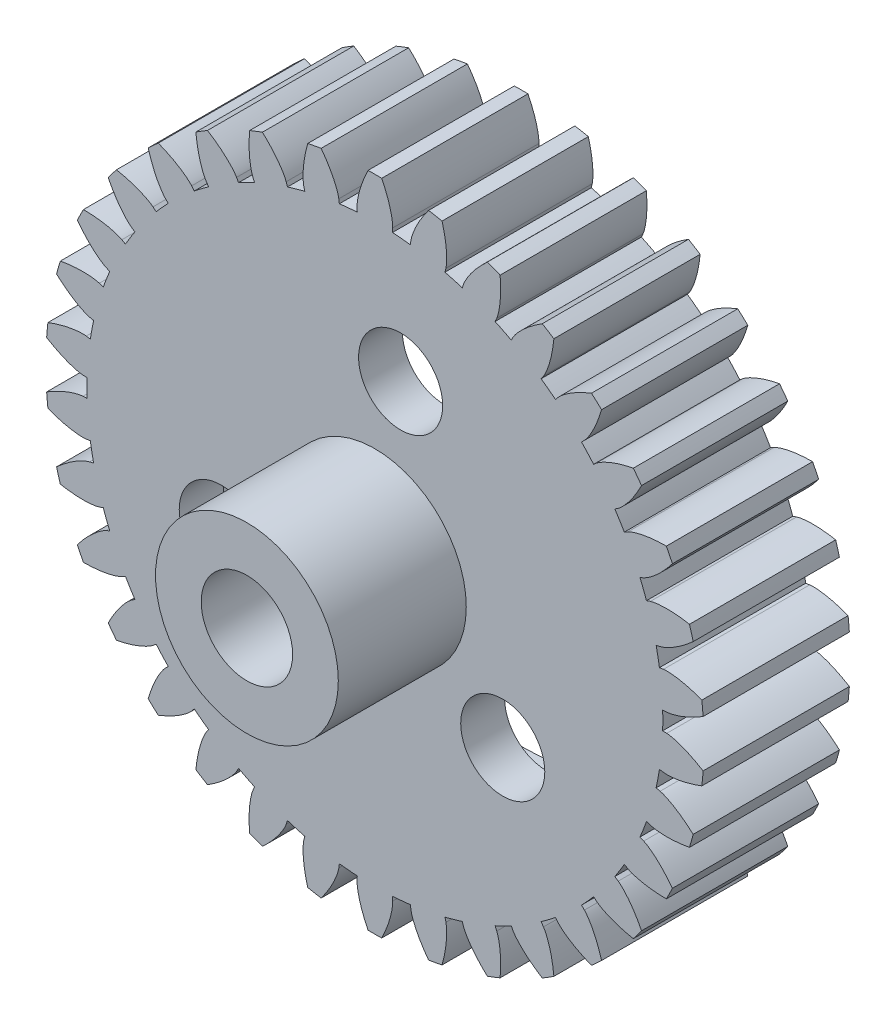
SolidWorks part; units mm, degrees
ref_plane "Płaszczyzna przednia" through (0, 0, 0) normal (0, 0, 1) x (1, 0, 0)
ref_plane "Płaszczyzna górna" through (0, 0, 0) normal (0, 1, 0) x (1, 0, 0)
ref_plane "Płaszczyzna prawa" through (0, 0, 0) normal (1, 0, 0) x (0, 0, -1)
sketch "Szkic1" plane through (0, 0, 0) normal (0, 0, 1) x (1, 0, 0)
  circle A0 centre (0, 0) radius 18
extrude "Dodanie-wyciągnięcie1" add sketch "Szkic1" along normal blind 8
sketch "Szkic2" plane through (0, 0, 8) normal (0, 0, 1) x (1, 0, 0)
  circle A0 centre (0, 0) radius 5
extrude "Dodanie-wyciągnięcie2" add sketch "Szkic2" along normal blind 7
sketch "Szkic3" plane through (0, 0, 15) normal (0, 0, 1) x (1, 0, 0)
  circle A0 centre (0, 0) radius 2.5
extrude "Wytnij-wyciągnięcie1" cut sketch "Szkic3" against normal through all
sketch "Szkic4" plane through (0, 0, 0) normal (0, 0, -1) x (-1, 0, 0)
  line L0 (15.967, 0.4999) -> (15.7423, 0.4928)
  line L1 (15.7423, -0.4928) -> (15.967, -0.4999)
  line L2 (15.3837, -3.3771) -> (15.6032, -3.4253)
  line L3 (14.5012, -6.1463) -> (14.7082, -6.234)
  line L4 (13.1249, -8.7063) -> (13.3122, -8.8305)
  line L5 (11.3017, -10.9697) -> (11.463, -11.1263)
  line L6 (9.0936, -12.8596) -> (9.2233, -13.0431)
  line L7 (6.5758, -14.3116) -> (6.6696, -14.5158)
  line L8 (3.8341, -15.2762) -> (3.8888, -15.4942)
  line L9 (0.9618, -15.7206) -> (0.9755, -15.945)
  line L10 (-1.9432, -15.6297) -> (-1.971, -15.8527)
  line L11 (-4.7821, -15.0065) -> (-4.8503, -15.2206)
  line L12 (-7.4581, -13.8722) -> (-7.5645, -14.0702)
  line L13 (-9.8801, -12.2656) -> (-10.0211, -12.4407)
  line L14 (-11.9657, -10.2413) -> (-12.1365, -10.3875)
  line L15 (-13.6438, -7.8682) -> (-13.8385, -7.9805)
  line L16 (-14.8573, -5.2272) -> (-15.0693, -5.3018)
  line L17 (-15.5648, -2.4082) -> (-15.7869, -2.4426)
  line L18 (-15.7423, 0.4928) -> (-15.967, 0.4999)
  line L19 (-15.3837, 3.3771) -> (-15.6032, 3.4253)
  line L20 (-14.5012, 6.1463) -> (-14.7082, 6.234)
  line L21 (-13.1249, 8.7063) -> (-13.3122, 8.8305)
  line L22 (-11.3017, 10.9697) -> (-11.463, 11.1263)
  line L23 (-9.0936, 12.8596) -> (-9.2233, 13.0431)
  line L24 (-6.5758, 14.3116) -> (-6.6696, 14.5158)
  line L25 (-3.8341, 15.2762) -> (-3.8888, 15.4942)
  line L26 (-0.9618, 15.7206) -> (-0.9755, 15.945)
  line L27 (1.9432, 15.6297) -> (1.971, 15.8527)
  line L28 (4.7821, 15.0065) -> (4.8503, 15.2206)
  line L29 (7.4581, 13.8722) -> (7.5645, 14.0702)
  line L30 (9.8801, 12.2656) -> (10.0211, 12.4407)
  line L31 (11.9657, 10.2413) -> (12.1365, 10.3875)
  line L32 (13.6438, 7.8682) -> (13.8385, 7.9805)
  line L33 (14.8573, 5.2272) -> (15.0693, 5.3018)
  line L34 (15.5648, 2.4082) -> (15.7869, 2.4426)
  line L35 (15.7869, -2.4426) -> (15.5648, -2.4082)
  line L36 (15.0693, -5.3018) -> (14.8573, -5.2272)
  line L37 (13.8385, -7.9805) -> (13.6438, -7.8682)
  line L38 (12.1365, -10.3875) -> (11.9657, -10.2413)
  line L39 (10.0211, -12.4407) -> (9.8801, -12.2656)
  line L40 (7.5645, -14.0702) -> (7.4581, -13.8722)
  line L41 (4.8503, -15.2206) -> (4.7821, -15.0065)
  line L42 (1.971, -15.8527) -> (1.9432, -15.6297)
  line L43 (-0.9755, -15.945) -> (-0.9618, -15.7206)
  line L44 (-3.8888, -15.4942) -> (-3.8341, -15.2762)
  line L45 (-6.6696, -14.5158) -> (-6.5758, -14.3116)
  line L46 (-9.2233, -13.0431) -> (-9.0936, -12.8596)
  line L47 (-11.463, -11.1263) -> (-11.3017, -10.9697)
  line L48 (-13.3122, -8.8305) -> (-13.1249, -8.7063)
  line L49 (-14.7082, -6.234) -> (-14.5012, -6.1463)
  line L50 (-15.6032, -3.4253) -> (-15.3837, -3.3771)
  line L51 (-15.967, -0.4999) -> (-15.7423, -0.4928)
  line L52 (-15.7869, 2.4426) -> (-15.5648, 2.4082)
  line L53 (-15.0693, 5.3018) -> (-14.8573, 5.2272)
  line L54 (-13.8385, 7.9805) -> (-13.6438, 7.8682)
  line L55 (-12.1365, 10.3875) -> (-11.9657, 10.2413)
  line L56 (-10.0211, 12.4407) -> (-9.8801, 12.2656)
  line L57 (-7.5645, 14.0702) -> (-7.4581, 13.8722)
  line L58 (-4.8503, 15.2206) -> (-4.7821, 15.0065)
  line L59 (-1.971, 15.8527) -> (-1.9432, 15.6297)
  line L60 (0.9755, 15.945) -> (0.9618, 15.7206)
  line L61 (3.8888, 15.4942) -> (3.8341, 15.2762)
  line L62 (6.6696, 14.5158) -> (6.5758, 14.3116)
  line L63 (9.2233, 13.0431) -> (9.0936, 12.8596)
  line L64 (11.463, 11.1263) -> (11.3017, 10.9697)
  line L65 (13.3122, 8.8305) -> (13.1249, 8.7063)
  line L66 (14.7082, 6.234) -> (14.5012, 6.1463)
  line L67 (15.6032, 3.4253) -> (15.3837, 3.3771)
  circle A1 centre (0, 0) radius 18
  arc A2 (15.7423, -0.4928) -> (15.7423, 0.4928) centre (0, 0) ccw
  arc A4 (15.3837, -3.3771) -> (15.5648, -2.4082) centre (0, 0) ccw
  arc A5 (14.5012, -6.1463) -> (14.8573, -5.2272) centre (0, 0) ccw
  arc A6 (13.1249, -8.7063) -> (13.6438, -7.8682) centre (0, 0) ccw
  arc A7 (11.3017, -10.9697) -> (11.9657, -10.2413) centre (0, 0) ccw
  arc A8 (9.0936, -12.8596) -> (9.8801, -12.2656) centre (0, 0) ccw
  arc A9 (6.5758, -14.3116) -> (7.4581, -13.8722) centre (0, 0) ccw
  arc A10 (3.8341, -15.2762) -> (4.7821, -15.0065) centre (0, 0) ccw
  arc A11 (0.9618, -15.7206) -> (1.9432, -15.6297) centre (0, 0) ccw
  arc A12 (-1.9432, -15.6297) -> (-0.9618, -15.7206) centre (0, 0) ccw
  arc A13 (-4.7821, -15.0065) -> (-3.8341, -15.2762) centre (0, 0) ccw
  arc A14 (-7.4581, -13.8722) -> (-6.5758, -14.3116) centre (0, 0) ccw
  arc A15 (-9.8801, -12.2656) -> (-9.0936, -12.8596) centre (0, 0) ccw
  arc A16 (-11.9657, -10.2413) -> (-11.3017, -10.9697) centre (0, 0) ccw
  arc A17 (-13.6438, -7.8682) -> (-13.1249, -8.7063) centre (0, 0) ccw
  arc A18 (-14.8573, -5.2272) -> (-14.5012, -6.1463) centre (0, 0) ccw
  arc A19 (-15.5648, -2.4082) -> (-15.3837, -3.3771) centre (0, 0) ccw
  arc A20 (-15.7423, 0.4928) -> (-15.7423, -0.4928) centre (0, 0) ccw
  arc A21 (-15.3837, 3.3771) -> (-15.5648, 2.4082) centre (0, 0) ccw
  arc A22 (-14.5012, 6.1463) -> (-14.8573, 5.2272) centre (0, 0) ccw
  arc A23 (-13.1249, 8.7063) -> (-13.6438, 7.8682) centre (0, 0) ccw
  arc A24 (-11.3017, 10.9697) -> (-11.9657, 10.2413) centre (0, 0) ccw
  arc A25 (-9.0936, 12.8596) -> (-9.8801, 12.2656) centre (0, 0) ccw
  arc A26 (-6.5758, 14.3116) -> (-7.4581, 13.8722) centre (0, 0) ccw
  arc A27 (-3.8341, 15.2762) -> (-4.7821, 15.0065) centre (0, 0) ccw
  arc A28 (-0.9618, 15.7206) -> (-1.9432, 15.6297) centre (0, 0) ccw
  arc A29 (1.9432, 15.6297) -> (0.9618, 15.7206) centre (0, 0) ccw
  arc A30 (4.7821, 15.0065) -> (3.8341, 15.2762) centre (0, 0) ccw
  arc A31 (7.4581, 13.8722) -> (6.5758, 14.3116) centre (0, 0) ccw
  arc A32 (9.8801, 12.2656) -> (9.0936, 12.8596) centre (0, 0) ccw
  arc A33 (11.9657, 10.2413) -> (11.3017, 10.9697) centre (0, 0) ccw
  arc A34 (13.6438, 7.8682) -> (13.1249, 8.7063) centre (0, 0) ccw
  arc A35 (14.8573, 5.2272) -> (14.5012, 6.1463) centre (0, 0) ccw
  arc A36 (15.5648, 2.4082) -> (15.3837, 3.3771) centre (0, 0) ccw
  spline S0 degree 4 poles (15.967, -0.4999) (15.9736, -0.5002) (15.9922, -0.5014) (16.0273, -0.5049) (16.0844, -0.5126) (16.1568, -0.525) (16.2501, -0.5441) (16.3593, -0.5705) (16.4786, -0.6036) (16.6076, -0.6441) (16.7354, -0.6883) (16.862, -0.736) (16.9874, -0.7867) (17.1381, -0.8519) (17.3174, -0.9353) (17.5245, -1.0403) (17.7565, -1.1683) (17.9894, -1.308) (18.2157, -1.4531) (18.4407, -1.6083) (18.6558, -1.7646) (18.8752, -1.9356) (19.0758, -2.0978) (19.2957, -2.2889) (19.4718, -2.4459) (19.6988, -2.6628) (19.8313, -2.7938) (19.9845, -2.9504) (20.0515, -3.0217) (20.0928, -3.0655) knots 0 0 0 0 0 0.005377 0.015084 0.028532 0.04661 0.064855 0.092111 0.119476 0.146842 0.174209 0.201575 0.228941 0.256307 0.307035 0.361767 0.4165 0.471232 0.525964 0.580697 0.635429 0.690161 0.744894 0.799626 0.854358 0.909091 0.954545 1 1 1 1 1 construction
  spline S1 degree 4 poles (15.967, -0.4999) (15.9736, -0.5002) (15.9922, -0.5014) (16.0273, -0.5049) (16.0844, -0.5126) (16.1568, -0.525) (16.2501, -0.5441) (16.3593, -0.5705) (16.4786, -0.6036) (16.6076, -0.6441) (16.7354, -0.6883) (16.862, -0.736) (16.9874, -0.7867) (17.1381, -0.8519) (17.3174, -0.9353) (17.5245, -1.0403) (17.7565, -1.1683) (17.9894, -1.308) (18.2157, -1.4531) (18.4407, -1.6083) (18.6558, -1.7646) (18.8752, -1.9356) (19.0758, -2.0978) (19.2957, -2.2889) (19.4718, -2.4459) (19.6496, -2.6158) (19.7355, -2.6996) (19.7792, -2.7428) knots 0 0 0 0 0 0.005377 0.015084 0.028532 0.04661 0.064855 0.092111 0.119476 0.146842 0.174209 0.201575 0.228941 0.256307 0.307035 0.361767 0.4165 0.471232 0.525964 0.580697 0.635429 0.690161 0.744894 0.799626 0.854358 0.909091 0.909091 0.909091 0.909091 0.909091
  spline S2 degree 4 poles (15.967, 0.4999) (15.9736, 0.5002) (15.9922, 0.5014) (16.0273, 0.5049) (16.0844, 0.5126) (16.1568, 0.525) (16.2501, 0.5441) (16.3593, 0.5705) (16.4786, 0.6036) (16.6076, 0.6441) (16.7354, 0.6883) (16.862, 0.736) (16.9874, 0.7867) (17.1381, 0.8519) (17.3174, 0.9353) (17.5245, 1.0403) (17.7565, 1.1683) (17.9894, 1.308) (18.2157, 1.4531) (18.4407, 1.6083) (18.6558, 1.7646) (18.8752, 1.9356) (19.0758, 2.0978) (19.2957, 2.2889) (19.4718, 2.4459) (19.6988, 2.6628) (19.8313, 2.7938) (19.9845, 2.9504) (20.0515, 3.0217) (20.0928, 3.0655) knots 0 0 0 0 0 0.005377 0.015084 0.028532 0.04661 0.064855 0.092111 0.119476 0.146842 0.174209 0.201575 0.228941 0.256307 0.307035 0.361767 0.4165 0.471232 0.525964 0.580697 0.635429 0.690161 0.744894 0.799626 0.854358 0.909091 0.954545 1 1 1 1 1 construction
  spline S3 degree 4 poles (15.967, 0.4999) (15.9736, 0.5002) (15.9922, 0.5014) (16.0273, 0.5049) (16.0844, 0.5126) (16.1568, 0.525) (16.2501, 0.5441) (16.3593, 0.5705) (16.4786, 0.6036) (16.6076, 0.6441) (16.7354, 0.6883) (16.862, 0.736) (16.9874, 0.7867) (17.1381, 0.8519) (17.3174, 0.9353) (17.5245, 1.0403) (17.7565, 1.1683) (17.9894, 1.308) (18.2157, 1.4531) (18.4407, 1.6083) (18.6558, 1.7646) (18.8752, 1.9356) (19.0758, 2.0978) (19.2957, 2.2889) (19.4718, 2.4459) (19.6496, 2.6158) (19.7355, 2.6996) (19.7792, 2.7428) knots 0 0 0 0 0 0.005377 0.015084 0.028532 0.04661 0.064855 0.092111 0.119476 0.146842 0.174209 0.201575 0.228941 0.256307 0.307035 0.361767 0.4165 0.471232 0.525964 0.580697 0.635429 0.690161 0.744894 0.799626 0.854358 0.909091 0.909091 0.909091 0.909091 0.909091
  spline S4 degree 4 poles (15.7869, -2.4426) (15.7935, -2.4435) (15.812, -2.4457) (15.8472, -2.4487) (15.9047, -2.4516) (15.9782, -2.4528) (16.0733, -2.4511) (16.1856, -2.4452) (16.309, -2.4346) (16.4432, -2.4185) (16.5769, -2.3985) (16.7102, -2.3749) (16.8427, -2.3481) (17.0028, -2.3117) (17.1944, -2.2627) (17.4173, -2.1975) (17.6688, -2.1144) (17.9234, -2.0198) (18.1725, -1.9188) (18.4222, -1.8075) (18.6624, -1.6934) (18.9095, -1.5657) (19.1364, -1.4431) (19.3877, -1.2956) (19.5897, -1.1737) (19.8527, -1.0022) (20.007, -0.8978) (20.1863, -0.772) (20.2653, -0.7142) (20.314, -0.6787) knots 0 0 0 0 0 0.005377 0.015084 0.028532 0.04661 0.064855 0.092111 0.119476 0.146842 0.174209 0.201575 0.228941 0.256307 0.307035 0.361767 0.4165 0.471232 0.525964 0.580697 0.635429 0.690161 0.744894 0.799626 0.854358 0.909091 0.954545 1 1 1 1 1 construction
  spline S5 degree 4 poles (15.7869, -2.4426) (15.7935, -2.4435) (15.812, -2.4457) (15.8472, -2.4487) (15.9047, -2.4516) (15.9782, -2.4528) (16.0733, -2.4511) (16.1856, -2.4452) (16.309, -2.4346) (16.4432, -2.4185) (16.5769, -2.3985) (16.7102, -2.3749) (16.8427, -2.3481) (17.0028, -2.3117) (17.1944, -2.2627) (17.4173, -2.1975) (17.6688, -2.1144) (17.9234, -2.0198) (18.1725, -1.9188) (18.4222, -1.8075) (18.6624, -1.6934) (18.9095, -1.5657) (19.1364, -1.4431) (19.3877, -1.2956) (19.5897, -1.1737) (19.7957, -1.0394) (19.8956, -0.9728) (19.9464, -0.9383) knots 0 0 0 0 0 0.005377 0.015084 0.028532 0.04661 0.064855 0.092111 0.119476 0.146842 0.174209 0.201575 0.228941 0.256307 0.307035 0.361767 0.4165 0.471232 0.525964 0.580697 0.635429 0.690161 0.744894 0.799626 0.854358 0.909091 0.909091 0.909091 0.909091 0.909091
  spline S6 degree 4 poles (15.6032, -3.4253) (15.6097, -3.4268) (15.6278, -3.4314) (15.6616, -3.4413) (15.7163, -3.4593) (15.7852, -3.4849) (15.8734, -3.5208) (15.9759, -3.5668) (16.0871, -3.6213) (16.2065, -3.6848) (16.324, -3.7517) (16.4397, -3.8218) (16.5536, -3.8947) (16.6898, -3.9865) (16.8507, -4.1014) (17.035, -4.2427) (17.2395, -4.4111) (17.4428, -4.5913) (17.6385, -4.7755) (17.8312, -4.9694) (18.0139, -5.1626) (18.1982, -5.3709) (18.3655, -5.5673) (18.5465, -5.7955) (18.6908, -5.9822) (18.8741, -6.2371) (18.9803, -6.3902) (19.1021, -6.5723) (19.1548, -6.6547) (19.1874, -6.7054) knots 0 0 0 0 0 0.005377 0.015084 0.028532 0.04661 0.064855 0.092111 0.119476 0.146842 0.174209 0.201575 0.228941 0.256307 0.307035 0.361767 0.4165 0.471232 0.525964 0.580697 0.635429 0.690161 0.744894 0.799626 0.854358 0.909091 0.954545 1 1 1 1 1 construction
  spline S7 degree 4 poles (15.6032, -3.4253) (15.6097, -3.4268) (15.6278, -3.4314) (15.6616, -3.4413) (15.7163, -3.4593) (15.7852, -3.4849) (15.8734, -3.5208) (15.9759, -3.5668) (16.0871, -3.6213) (16.2065, -3.6848) (16.324, -3.7517) (16.4397, -3.8218) (16.5536, -3.8947) (16.6898, -3.9865) (16.8507, -4.1014) (17.035, -4.2427) (17.2395, -4.4111) (17.4428, -4.5913) (17.6385, -4.7755) (17.8312, -4.9694) (18.0139, -5.1626) (18.1982, -5.3709) (18.3655, -5.5673) (18.5465, -5.7955) (18.6908, -5.9822) (18.8344, -6.1818) (18.9035, -6.28) (18.9384, -6.3306) knots 0 0 0 0 0 0.005377 0.015084 0.028532 0.04661 0.064855 0.092111 0.119476 0.146842 0.174209 0.201575 0.228941 0.256307 0.307035 0.361767 0.4165 0.471232 0.525964 0.580697 0.635429 0.690161 0.744894 0.799626 0.854358 0.909091 0.909091 0.909091 0.909091 0.909091
  spline S8 degree 4 poles (15.0693, -5.3018) (15.0756, -5.3039) (15.0934, -5.3095) (15.1274, -5.3189) (15.1834, -5.3324) (15.2554, -5.347) (15.3493, -5.3628) (15.4607, -5.3777) (15.5839, -5.3899) (15.7188, -5.3988) (15.8539, -5.4037) (15.9893, -5.405) (16.1244, -5.403) (16.2886, -5.3966) (16.4858, -5.3836) (16.7169, -5.3605) (16.9794, -5.325) (17.2471, -5.2789) (17.5105, -5.2253) (17.7764, -5.1618) (18.0335, -5.0938) (18.2999, -5.0136) (18.5454, -4.9348) (18.8195, -4.836) (19.0405, -4.7533) (19.3305, -4.6331) (19.5014, -4.5588) (19.7008, -4.4681) (19.789, -4.4258) (19.8434, -4.3998) knots 0 0 0 0 0 0.005377 0.015084 0.028532 0.04661 0.064855 0.092111 0.119476 0.146842 0.174209 0.201575 0.228941 0.256307 0.307035 0.361767 0.4165 0.471232 0.525964 0.580697 0.635429 0.690161 0.744894 0.799626 0.854358 0.909091 0.954545 1 1 1 1 1 construction
  spline S9 degree 4 poles (15.0693, -5.3018) (15.0756, -5.3039) (15.0934, -5.3095) (15.1274, -5.3189) (15.1834, -5.3324) (15.2554, -5.347) (15.3493, -5.3628) (15.4607, -5.3777) (15.5839, -5.3899) (15.7188, -5.3988) (15.8539, -5.4037) (15.9893, -5.405) (16.1244, -5.403) (16.2886, -5.3966) (16.4858, -5.3836) (16.7169, -5.3605) (16.9794, -5.325) (17.2471, -5.2789) (17.5105, -5.2253) (17.7764, -5.1618) (18.0335, -5.0938) (18.2999, -5.0136) (18.5454, -4.9348) (18.8195, -4.836) (19.0405, -4.7533) (19.2676, -4.6591) (19.378, -4.612) (19.4344, -4.5874) knots 0 0 0 0 0 0.005377 0.015084 0.028532 0.04661 0.064855 0.092111 0.119476 0.146842 0.174209 0.201575 0.228941 0.256307 0.307035 0.361767 0.4165 0.471232 0.525964 0.580697 0.635429 0.690161 0.744894 0.799626 0.854358 0.909091 0.909091 0.909091 0.909091 0.909091
  spline S10 degree 4 poles (14.7082, -6.234) (14.7142, -6.2367) (14.7312, -6.2446) (14.7626, -6.2606) (14.8131, -6.2883) (14.8761, -6.3261) (14.9562, -6.3775) (15.0485, -6.4417) (15.1478, -6.5157) (15.2535, -6.6) (15.3567, -6.6873) (15.4575, -6.7776) (15.5561, -6.8701) (15.6731, -6.9854) (15.8101, -7.1279) (15.9653, -7.3007) (16.1354, -7.5038) (16.3021, -7.7182) (16.4607, -7.9352) (16.6144, -8.1613) (16.7586, -8.3847) (16.9014, -8.6234) (17.0298, -8.8471) (17.1658, -9.1048) (17.2734, -9.3148) (17.4067, -9.599) (17.4829, -9.769) (17.5692, -9.9704) (17.6059, -10.0611) (17.6286, -10.1169) knots 0 0 0 0 0 0.005377 0.015084 0.028532 0.04661 0.064855 0.092111 0.119476 0.146842 0.174209 0.201575 0.228941 0.256307 0.307035 0.361767 0.4165 0.471232 0.525964 0.580697 0.635429 0.690161 0.744894 0.799626 0.854358 0.909091 0.954545 1 1 1 1 1 construction
  spline S11 degree 4 poles (14.7082, -6.234) (14.7142, -6.2367) (14.7312, -6.2446) (14.7626, -6.2606) (14.8131, -6.2883) (14.8761, -6.3261) (14.9562, -6.3775) (15.0485, -6.4417) (15.1478, -6.5157) (15.2535, -6.6) (15.3567, -6.6873) (15.4575, -6.7776) (15.5561, -6.8701) (15.6731, -6.9854) (15.8101, -7.1279) (15.9653, -7.3007) (16.1354, -7.5038) (16.3021, -7.7182) (16.4607, -7.9352) (16.6144, -8.1613) (16.7586, -8.3847) (16.9014, -8.6234) (17.0298, -8.8471) (17.1658, -9.1048) (17.2734, -9.3148) (17.3778, -9.5374) (17.4277, -9.6466) (17.4527, -9.7027) knots 0 0 0 0 0 0.005377 0.015084 0.028532 0.04661 0.064855 0.092111 0.119476 0.146842 0.174209 0.201575 0.228941 0.256307 0.307035 0.361767 0.4165 0.471232 0.525964 0.580697 0.635429 0.690161 0.744894 0.799626 0.854358 0.909091 0.909091 0.909091 0.909091 0.909091
  spline S12 degree 4 poles (13.8385, -7.9805) (13.8443, -7.9838) (13.8608, -7.9925) (13.8925, -8.008) (13.945, -8.0315) (14.0132, -8.0591) (14.1025, -8.092) (14.2093, -8.127) (14.3282, -8.1617) (14.4591, -8.1952) (14.5911, -8.2249) (14.7238, -8.251) (14.8571, -8.2738) (15.0196, -8.2978) (15.2159, -8.3212) (15.4473, -8.341) (15.7119, -8.3543) (15.9835, -8.3581) (16.2522, -8.3539) (16.5253, -8.3403) (16.7904, -8.3207) (17.067, -8.2909) (17.3229, -8.2585) (17.6105, -8.2118) (17.8429, -8.171) (18.1501, -8.1062) (18.3317, -8.0645) (18.5443, -8.012) (18.6388, -7.9867) (18.697, -7.9711) knots 0 0 0 0 0 0.005377 0.015084 0.028532 0.04661 0.064855 0.092111 0.119476 0.146842 0.174209 0.201575 0.228941 0.256307 0.307035 0.361767 0.4165 0.471232 0.525964 0.580697 0.635429 0.690161 0.744894 0.799626 0.854358 0.909091 0.954545 1 1 1 1 1 construction
  spline S13 degree 4 poles (13.8385, -7.9805) (13.8443, -7.9838) (13.8608, -7.9925) (13.8925, -8.008) (13.945, -8.0315) (14.0132, -8.0591) (14.1025, -8.092) (14.2093, -8.127) (14.3282, -8.1617) (14.4591, -8.1952) (14.5911, -8.2249) (14.7238, -8.251) (14.8571, -8.2738) (15.0196, -8.2978) (15.2159, -8.3212) (15.4473, -8.341) (15.7119, -8.3543) (15.9835, -8.3581) (16.2522, -8.3539) (16.5253, -8.3403) (16.7904, -8.3207) (17.067, -8.2909) (17.3229, -8.2585) (17.6105, -8.2118) (17.8429, -8.171) (18.0835, -8.1202) (18.2006, -8.0942) (18.2605, -8.0804) knots 0 0 0 0 0 0.005377 0.015084 0.028532 0.04661 0.064855 0.092111 0.119476 0.146842 0.174209 0.201575 0.228941 0.256307 0.307035 0.361767 0.4165 0.471232 0.525964 0.580697 0.635429 0.690161 0.744894 0.799626 0.854358 0.909091 0.909091 0.909091 0.909091 0.909091
  spline S14 degree 4 poles (13.3122, -8.8305) (13.3177, -8.8343) (13.3329, -8.8451) (13.3608, -8.8666) (13.4054, -8.9031) (13.4604, -8.9518) (13.5296, -9.0171) (13.6086, -9.0971) (13.6926, -9.1881) (13.781, -9.2904) (13.8664, -9.3953) (13.949, -9.5025) (14.0288, -9.6116) (14.1227, -9.7463) (14.2312, -9.9116) (14.352, -10.11) (14.4818, -10.3409) (14.6063, -10.5823) (14.7223, -10.8248) (14.8319, -11.0752) (14.9325, -11.3213) (15.0291, -11.5822) (15.1142, -11.8257) (15.2006, -12.104) (15.2677, -12.3302) (15.3465, -12.634) (15.3902, -12.8152) (15.438, -13.0289) (15.4574, -13.1248) (15.4694, -13.1839) knots 0 0 0 0 0 0.005377 0.015084 0.028532 0.04661 0.064855 0.092111 0.119476 0.146842 0.174209 0.201575 0.228941 0.256307 0.307035 0.361767 0.4165 0.471232 0.525964 0.580697 0.635429 0.690161 0.744894 0.799626 0.854358 0.909091 0.954545 1 1 1 1 1 construction
  spline S15 degree 4 poles (13.3122, -8.8305) (13.3177, -8.8343) (13.3329, -8.8451) (13.3608, -8.8666) (13.4054, -8.9031) (13.4604, -8.9518) (13.5296, -9.0171) (13.6086, -9.0971) (13.6926, -9.1881) (13.781, -9.2904) (13.8664, -9.3953) (13.949, -9.5025) (14.0288, -9.6116) (14.1227, -9.7463) (14.2312, -9.9116) (14.352, -10.11) (14.4818, -10.3409) (14.6063, -10.5823) (14.7223, -10.8248) (14.8319, -11.0752) (14.9325, -11.3213) (15.0291, -11.5822) (15.1142, -11.8257) (15.2006, -12.104) (15.2677, -12.3302) (15.3294, -12.5682) (15.3584, -12.6846) (15.3727, -12.7444) knots 0 0 0 0 0 0.005377 0.015084 0.028532 0.04661 0.064855 0.092111 0.119476 0.146842 0.174209 0.201575 0.228941 0.256307 0.307035 0.361767 0.4165 0.471232 0.525964 0.580697 0.635429 0.690161 0.744894 0.799626 0.854358 0.909091 0.909091 0.909091 0.909091 0.909091
  spline S16 degree 4 poles (12.1365, -10.3875) (12.1416, -10.3917) (12.1561, -10.4033) (12.1845, -10.4243) (12.2318, -10.4572) (12.2937, -10.4968) (12.3755, -10.5455) (12.474, -10.5996) (12.5845, -10.6555) (12.7071, -10.7125) (12.8313, -10.7659) (12.957, -10.816) (13.0838, -10.8629) (13.2391, -10.9163) (13.4278, -10.9755) (13.6516, -11.0374) (13.9092, -11.0991) (14.1755, -11.1528) (14.4405, -11.198) (14.7114, -11.2348) (14.9756, -11.2643) (15.253, -11.2857) (15.5104, -11.301) (15.8017, -11.3079) (16.0376, -11.3105) (16.3515, -11.3032) (16.5377, -11.2957) (16.7564, -11.2831) (16.8539, -11.2755) (16.914, -11.271) knots 0 0 0 0 0 0.005377 0.015084 0.028532 0.04661 0.064855 0.092111 0.119476 0.146842 0.174209 0.201575 0.228941 0.256307 0.307035 0.361767 0.4165 0.471232 0.525964 0.580697 0.635429 0.690161 0.744894 0.799626 0.854358 0.909091 0.954545 1 1 1 1 1 construction
  spline S17 degree 4 poles (12.1365, -10.3875) (12.1416, -10.3917) (12.1561, -10.4033) (12.1845, -10.4243) (12.2318, -10.4572) (12.2937, -10.4968) (12.3755, -10.5455) (12.474, -10.5996) (12.5845, -10.6555) (12.7071, -10.7125) (12.8313, -10.7659) (12.957, -10.816) (13.0838, -10.8629) (13.2391, -10.9163) (13.4278, -10.9755) (13.6516, -11.0374) (13.9092, -11.0991) (14.1755, -11.1528) (14.4405, -11.198) (14.7114, -11.2348) (14.9756, -11.2643) (15.253, -11.2857) (15.5104, -11.301) (15.8017, -11.3079) (16.0376, -11.3105) (16.2835, -11.3048) (16.4034, -11.3008) (16.4648, -11.2982) knots 0 0 0 0 0 0.005377 0.015084 0.028532 0.04661 0.064855 0.092111 0.119476 0.146842 0.174209 0.201575 0.228941 0.256307 0.307035 0.361767 0.4165 0.471232 0.525964 0.580697 0.635429 0.690161 0.744894 0.799626 0.854358 0.909091 0.909091 0.909091 0.909091 0.909091
  spline S18 degree 4 poles (11.463, -11.1263) (11.4677, -11.131) (11.4806, -11.1444) (11.5041, -11.1707) (11.5412, -11.2148) (11.5863, -11.2727) (11.6424, -11.3497) (11.7053, -11.4428) (11.7712, -11.5477) (11.8392, -11.6645) (11.9039, -11.7832) (11.9654, -11.9038) (12.0238, -12.0257) (12.0913, -12.1754) (12.1676, -12.3578) (12.2499, -12.575) (12.3351, -12.8258) (12.4131, -13.086) (12.4826, -13.3457) (12.5443, -13.612) (12.598, -13.8724) (12.645, -14.1466) (12.6839, -14.4016) (12.7176, -14.691) (12.742, -14.9256) (12.7637, -15.2388) (12.7734, -15.4249) (12.781, -15.6438) (12.7825, -15.7417) (12.7835, -15.8019) knots 0 0 0 0 0 0.005377 0.015084 0.028532 0.04661 0.064855 0.092111 0.119476 0.146842 0.174209 0.201575 0.228941 0.256307 0.307035 0.361767 0.4165 0.471232 0.525964 0.580697 0.635429 0.690161 0.744894 0.799626 0.854358 0.909091 0.954545 1 1 1 1 1 construction
  spline S19 degree 4 poles (11.463, -11.1263) (11.4677, -11.131) (11.4806, -11.1444) (11.5041, -11.1707) (11.5412, -11.2148) (11.5863, -11.2727) (11.6424, -11.3497) (11.7053, -11.4428) (11.7712, -11.5477) (11.8392, -11.6645) (11.9039, -11.7832) (11.9654, -11.9038) (12.0238, -12.0257) (12.0913, -12.1754) (12.1676, -12.3578) (12.2499, -12.575) (12.3351, -12.8258) (12.4131, -13.086) (12.4826, -13.3457) (12.5443, -13.612) (12.598, -13.8724) (12.645, -14.1466) (12.6839, -14.4016) (12.7176, -14.691) (12.742, -14.9256) (12.759, -15.1709) (12.7661, -15.2907) (12.7692, -15.3521) knots 0 0 0 0 0 0.005377 0.015084 0.028532 0.04661 0.064855 0.092111 0.119476 0.146842 0.174209 0.201575 0.228941 0.256307 0.307035 0.361767 0.4165 0.471232 0.525964 0.580697 0.635429 0.690161 0.744894 0.799626 0.854358 0.909091 0.909091 0.909091 0.909091 0.909091
  spline S20 degree 4 poles (10.0211, -12.4407) (10.0254, -12.4458) (10.0376, -12.4599) (10.0615, -12.4857) (10.102, -12.5267) (10.1556, -12.577) (10.227, -12.6399) (10.314, -12.7112) (10.4123, -12.7865) (10.5223, -12.865) (10.6346, -12.9404) (10.749, -13.0127) (10.865, -13.0821) (11.0078, -13.1631) (11.1824, -13.2559) (11.3911, -13.3579) (11.633, -13.4659) (11.8848, -13.5676) (12.137, -13.6607) (12.3965, -13.7468) (12.6508, -13.8242) (12.9195, -13.8963) (13.1698, -13.9586) (13.4549, -14.0189) (13.6863, -14.0648) (13.9962, -14.1153) (14.1805, -14.1421) (14.3978, -14.17) (14.4951, -14.1805) (14.555, -14.187) knots 0 0 0 0 0 0.005377 0.015084 0.028532 0.04661 0.064855 0.092111 0.119476 0.146842 0.174209 0.201575 0.228941 0.256307 0.307035 0.361767 0.4165 0.471232 0.525964 0.580697 0.635429 0.690161 0.744894 0.799626 0.854358 0.909091 0.954545 1 1 1 1 1 construction
  spline S21 degree 4 poles (10.0211, -12.4407) (10.0254, -12.4458) (10.0376, -12.4599) (10.0615, -12.4857) (10.102, -12.5267) (10.1556, -12.577) (10.227, -12.6399) (10.314, -12.7112) (10.4123, -12.7865) (10.5223, -12.865) (10.6346, -12.9404) (10.749, -13.0127) (10.865, -13.0821) (11.0078, -13.1631) (11.1824, -13.2559) (11.3911, -13.3579) (11.633, -13.4659) (11.8848, -13.5676) (12.137, -13.6607) (12.3965, -13.7468) (12.6508, -13.8242) (12.9195, -13.8963) (13.1698, -13.9586) (13.4549, -14.0189) (13.6863, -14.0648) (13.929, -14.1044) (14.0476, -14.1225) (14.1085, -14.1312) knots 0 0 0 0 0 0.005377 0.015084 0.028532 0.04661 0.064855 0.092111 0.119476 0.146842 0.174209 0.201575 0.228941 0.256307 0.307035 0.361767 0.4165 0.471232 0.525964 0.580697 0.635429 0.690161 0.744894 0.799626 0.854358 0.909091 0.909091 0.909091 0.909091 0.909091
  spline S22 degree 4 poles (9.2233, -13.0431) (9.2271, -13.0486) (9.2373, -13.0642) (9.2556, -13.0943) (9.2839, -13.1445) (9.3177, -13.2098) (9.3587, -13.2957) (9.4034, -13.3988) (9.4489, -13.514) (9.4943, -13.6413) (9.5361, -13.7699) (9.5743, -13.8997) (9.6094, -14.0303) (9.6482, -14.1899) (9.6897, -14.3832) (9.7307, -14.6118) (9.7684, -14.874) (9.7972, -15.1441) (9.8178, -15.4121) (9.8295, -15.6852) (9.8344, -15.9511) (9.8302, -16.2292) (9.8216, -16.487) (9.8016, -16.7777) (9.7825, -17.0128) (9.7463, -17.3247) (9.7216, -17.5094) (9.6889, -17.726) (9.6724, -17.8224) (9.6623, -17.8818) knots 0 0 0 0 0 0.005377 0.015084 0.028532 0.04661 0.064855 0.092111 0.119476 0.146842 0.174209 0.201575 0.228941 0.256307 0.307035 0.361767 0.4165 0.471232 0.525964 0.580697 0.635429 0.690161 0.744894 0.799626 0.854358 0.909091 0.954545 1 1 1 1 1 construction
  spline S23 degree 4 poles (9.2233, -13.0431) (9.2271, -13.0486) (9.2373, -13.0642) (9.2556, -13.0943) (9.2839, -13.1445) (9.3177, -13.2098) (9.3587, -13.2957) (9.4034, -13.3988) (9.4489, -13.514) (9.4943, -13.6413) (9.5361, -13.7699) (9.5743, -13.8997) (9.6094, -14.0303) (9.6482, -14.1899) (9.6897, -14.3832) (9.7307, -14.6118) (9.7684, -14.874) (9.7972, -15.1441) (9.8178, -15.4121) (9.8295, -15.6852) (9.8344, -15.9511) (9.8302, -16.2292) (9.8216, -16.487) (9.8016, -16.7777) (9.7825, -17.0128) (9.7541, -17.2571) (9.739, -17.3761) (9.7308, -17.4371) knots 0 0 0 0 0 0.005377 0.015084 0.028532 0.04661 0.064855 0.092111 0.119476 0.146842 0.174209 0.201575 0.228941 0.256307 0.307035 0.361767 0.4165 0.471232 0.525964 0.580697 0.635429 0.690161 0.744894 0.799626 0.854358 0.909091 0.909091 0.909091 0.909091 0.909091
  spline S24 degree 4 poles (7.5645, -14.0702) (7.5678, -14.076) (7.5771, -14.0921) (7.596, -14.122) (7.6283, -14.1696) (7.6717, -14.229) (7.7303, -14.3039) (7.8027, -14.3899) (7.8855, -14.482) (7.9792, -14.5794) (8.0758, -14.6741) (8.1749, -14.7662) (8.2761, -14.8558) (8.4017, -14.9617) (8.5563, -15.085) (8.7426, -15.2236) (8.9605, -15.3742) (9.1894, -15.5204) (9.4202, -15.6583) (9.6594, -15.7905) (9.8952, -15.9134) (10.1461, -16.0337) (10.3807, -16.1408) (10.6498, -16.2525) (10.8688, -16.3402) (11.1642, -16.4468) (11.3405, -16.507) (11.5489, -16.5743) (11.6426, -16.6025) (11.7003, -16.6199) knots 0 0 0 0 0 0.005377 0.015084 0.028532 0.04661 0.064855 0.092111 0.119476 0.146842 0.174209 0.201575 0.228941 0.256307 0.307035 0.361767 0.4165 0.471232 0.525964 0.580697 0.635429 0.690161 0.744894 0.799626 0.854358 0.909091 0.954545 1 1 1 1 1 construction
  spline S25 degree 4 poles (7.5645, -14.0702) (7.5678, -14.076) (7.5771, -14.0921) (7.596, -14.122) (7.6283, -14.1696) (7.6717, -14.229) (7.7303, -14.3039) (7.8027, -14.3899) (7.8855, -14.482) (7.9792, -14.5794) (8.0758, -14.6741) (8.1749, -14.7662) (8.2761, -14.8558) (8.4017, -14.9617) (8.5563, -15.085) (8.7426, -15.2236) (8.9605, -15.3742) (9.1894, -15.5204) (9.4202, -15.6583) (9.6594, -15.7905) (9.8952, -15.9134) (10.1461, -16.0337) (10.3807, -16.1408) (10.6498, -16.2525) (10.8688, -16.3402) (11.1001, -16.4237) (11.2134, -16.4632) (11.2716, -16.483) knots 0 0 0 0 0 0.005377 0.015084 0.028532 0.04661 0.064855 0.092111 0.119476 0.146842 0.174209 0.201575 0.228941 0.256307 0.307035 0.361767 0.4165 0.471232 0.525964 0.580697 0.635429 0.690161 0.744894 0.799626 0.854358 0.909091 0.909091 0.909091 0.909091 0.909091
  spline S26 degree 4 poles (6.6696, -14.5158) (6.6723, -14.5219) (6.6795, -14.5391) (6.692, -14.5721) (6.7106, -14.6266) (6.7318, -14.697) (6.7562, -14.789) (6.7813, -14.8985) (6.8048, -15.0201) (6.8261, -15.1536) (6.8435, -15.2877) (6.8572, -15.4223) (6.8677, -15.5571) (6.8765, -15.7211) (6.8818, -15.9188) (6.8801, -16.151) (6.8689, -16.4157) (6.8477, -16.6865) (6.8187, -16.9537) (6.78, -17.2243) (6.736, -17.4866) (6.6808, -17.7592) (6.6249, -18.011) (6.5519, -18.2931) (6.4898, -18.5207) (6.3969, -18.8206) (6.3387, -18.9976) (6.2668, -19.2045) (6.2328, -19.2962) (6.212, -19.3528) knots 0 0 0 0 0 0.005377 0.015084 0.028532 0.04661 0.064855 0.092111 0.119476 0.146842 0.174209 0.201575 0.228941 0.256307 0.307035 0.361767 0.4165 0.471232 0.525964 0.580697 0.635429 0.690161 0.744894 0.799626 0.854358 0.909091 0.954545 1 1 1 1 1 construction
  spline S27 degree 4 poles (6.6696, -14.5158) (6.6723, -14.5219) (6.6795, -14.5391) (6.692, -14.5721) (6.7106, -14.6266) (6.7318, -14.697) (6.7562, -14.789) (6.7813, -14.8985) (6.8048, -15.0201) (6.8261, -15.1536) (6.8435, -15.2877) (6.8572, -15.4223) (6.8677, -15.5571) (6.8765, -15.7211) (6.8818, -15.9188) (6.8801, -16.151) (6.8689, -16.4157) (6.8477, -16.6865) (6.8187, -16.9537) (6.78, -17.2243) (6.736, -17.4866) (6.6808, -17.7592) (6.6249, -18.011) (6.5519, -18.2931) (6.4898, -18.5207) (6.4171, -18.7556) (6.3803, -18.8698) (6.3611, -18.9282) knots 0 0 0 0 0 0.005377 0.015084 0.028532 0.04661 0.064855 0.092111 0.119476 0.146842 0.174209 0.201575 0.228941 0.256307 0.307035 0.361767 0.4165 0.471232 0.525964 0.580697 0.635429 0.690161 0.744894 0.799626 0.854358 0.909091 0.909091 0.909091 0.909091 0.909091
  spline S28 degree 4 poles (4.8503, -15.2206) (4.8525, -15.2269) (4.8587, -15.2445) (4.8717, -15.2773) (4.8947, -15.3301) (4.9265, -15.3964) (4.9704, -15.4808) (5.0257, -15.5787) (5.0902, -15.6844) (5.1644, -15.7974) (5.2419, -15.9082) (5.3224, -16.0169) (5.4055, -16.1236) (5.5094, -16.2507) (5.6387, -16.4003) (5.7964, -16.5708) (5.983, -16.7589) (6.1811, -16.9447) (6.3826, -17.1227) (6.5935, -17.2966) (6.8027, -17.4607) (7.0272, -17.625) (7.2381, -17.7735) (7.4821, -17.9327) (7.6813, -18.0591) (7.952, -18.2181) (8.1142, -18.3097) (8.3068, -18.4142) (8.3937, -18.4591) (8.4472, -18.4868) knots 0 0 0 0 0 0.005377 0.015084 0.028532 0.04661 0.064855 0.092111 0.119476 0.146842 0.174209 0.201575 0.228941 0.256307 0.307035 0.361767 0.4165 0.471232 0.525964 0.580697 0.635429 0.690161 0.744894 0.799626 0.854358 0.909091 0.954545 1 1 1 1 1 construction
  spline S29 degree 4 poles (4.8503, -15.2206) (4.8525, -15.2269) (4.8587, -15.2445) (4.8717, -15.2773) (4.8947, -15.3301) (4.9265, -15.3964) (4.9704, -15.4808) (5.0257, -15.5787) (5.0902, -15.6844) (5.1644, -15.7974) (5.2419, -15.9082) (5.3224, -16.0169) (5.4055, -16.1236) (5.5094, -16.2507) (5.6387, -16.4003) (5.7964, -16.5708) (5.983, -16.7589) (6.1811, -16.9447) (6.3826, -17.1227) (6.5935, -17.2966) (6.8027, -17.4607) (7.0272, -17.625) (7.2381, -17.7735) (7.4821, -17.9327) (7.6813, -18.0591) (7.8933, -18.1837) (7.9974, -18.2434) (8.051, -18.2735) knots 0 0 0 0 0 0.005377 0.015084 0.028532 0.04661 0.064855 0.092111 0.119476 0.146842 0.174209 0.201575 0.228941 0.256307 0.307035 0.361767 0.4165 0.471232 0.525964 0.580697 0.635429 0.690161 0.744894 0.799626 0.854358 0.909091 0.909091 0.909091 0.909091 0.909091
  spline S30 degree 4 poles (3.8888, -15.4942) (3.8903, -15.5007) (3.8942, -15.5189) (3.9004, -15.5536) (3.9087, -15.6106) (3.9166, -15.6837) (3.9237, -15.7786) (3.9282, -15.8909) (3.929, -16.0148) (3.9254, -16.1499) (3.9178, -16.2849) (3.9066, -16.4198) (3.8922, -16.5542) (3.8707, -16.717) (3.8395, -16.9123) (3.7952, -17.1402) (3.7356, -17.3983) (3.665, -17.6606) (3.5873, -17.918) (3.4996, -18.1769) (3.4082, -18.4265) (3.3038, -18.6844) (3.2026, -18.9216) (3.079, -19.1855) (2.9762, -19.3978) (2.8297, -19.6756) (2.74, -19.8388) (2.6313, -20.029) (2.581, -20.113) (2.5501, -20.1647) knots 0 0 0 0 0 0.005377 0.015084 0.028532 0.04661 0.064855 0.092111 0.119476 0.146842 0.174209 0.201575 0.228941 0.256307 0.307035 0.361767 0.4165 0.471232 0.525964 0.580697 0.635429 0.690161 0.744894 0.799626 0.854358 0.909091 0.954545 1 1 1 1 1 construction
  spline S31 degree 4 poles (3.8888, -15.4942) (3.8903, -15.5007) (3.8942, -15.5189) (3.9004, -15.5536) (3.9087, -15.6106) (3.9166, -15.6837) (3.9237, -15.7786) (3.9282, -15.8909) (3.929, -16.0148) (3.9254, -16.1499) (3.9178, -16.2849) (3.9066, -16.4198) (3.8922, -16.5542) (3.8707, -16.717) (3.8395, -16.9123) (3.7952, -17.1402) (3.7356, -17.3983) (3.665, -17.6606) (3.5873, -17.918) (3.4996, -18.1769) (3.4082, -18.4265) (3.3038, -18.6844) (3.2026, -18.9216) (3.079, -19.1855) (2.9762, -19.3978) (2.8615, -19.6153) (2.8044, -19.7209) (2.7747, -19.7748) knots 0 0 0 0 0 0.005377 0.015084 0.028532 0.04661 0.064855 0.092111 0.119476 0.146842 0.174209 0.201575 0.228941 0.256307 0.307035 0.361767 0.4165 0.471232 0.525964 0.580697 0.635429 0.690161 0.744894 0.799626 0.854358 0.909091 0.909091 0.909091 0.909091 0.909091
  spline S32 degree 4 poles (1.971, -15.8527) (1.9719, -15.8593) (1.9748, -15.8777) (1.9816, -15.9123) (1.9945, -15.9684) (2.0135, -16.0394) (2.0411, -16.1305) (2.0775, -16.2369) (2.1215, -16.3527) (2.1737, -16.4773) (2.2295, -16.6005) (2.2887, -16.7222) (2.3507, -16.8423) (2.4296, -16.9864) (2.5291, -17.1572) (2.6528, -17.3538) (2.8016, -17.5729) (2.9623, -17.792) (3.1276, -18.0039) (3.303, -18.2136) (3.4784, -18.4134) (3.6689, -18.6161) (3.849, -18.8008) (4.0596, -19.0022) (4.2321, -19.1631) (4.469, -19.3691) (4.6117, -19.489) (4.7817, -19.627) (4.8589, -19.6871) (4.9064, -19.7242) knots 0 0 0 0 0 0.005377 0.015084 0.028532 0.04661 0.064855 0.092111 0.119476 0.146842 0.174209 0.201575 0.228941 0.256307 0.307035 0.361767 0.4165 0.471232 0.525964 0.580697 0.635429 0.690161 0.744894 0.799626 0.854358 0.909091 0.954545 1 1 1 1 1 construction
  spline S33 degree 4 poles (1.971, -15.8527) (1.9719, -15.8593) (1.9748, -15.8777) (1.9816, -15.9123) (1.9945, -15.9684) (2.0135, -16.0394) (2.0411, -16.1305) (2.0775, -16.2369) (2.1215, -16.3527) (2.1737, -16.4773) (2.2295, -16.6005) (2.2887, -16.7222) (2.3507, -16.8423) (2.4296, -16.9864) (2.5291, -17.1572) (2.6528, -17.3538) (2.8016, -17.5729) (2.9623, -17.792) (3.1276, -18.0039) (3.303, -18.2136) (3.4784, -18.4134) (3.6689, -18.6161) (3.849, -18.8008) (4.0596, -19.0022) (4.2321, -19.1631) (4.4176, -19.3244) (4.509, -19.4023) (4.5561, -19.4417) knots 0 0 0 0 0 0.005377 0.015084 0.028532 0.04661 0.064855 0.092111 0.119476 0.146842 0.174209 0.201575 0.228941 0.256307 0.307035 0.361767 0.4165 0.471232 0.525964 0.580697 0.635429 0.690161 0.744894 0.799626 0.854358 0.909091 0.909091 0.909091 0.909091 0.909091
  spline S34 degree 4 poles (0.9755, -15.945) (0.9758, -15.9516) (0.9763, -15.9702) (0.976, -16.0055) (0.9737, -16.063) (0.968, -16.1363) (0.9576, -16.2309) (0.9414, -16.3422) (0.9194, -16.464) (0.891, -16.5962) (0.8588, -16.7275) (0.823, -16.858) (0.7841, -16.9875) (0.7331, -17.1436) (0.6665, -17.3298) (0.5811, -17.5457) (0.4751, -17.7885) (0.3574, -18.0333) (0.2338, -18.2721) (0.1, -18.5104) (-0.0357, -18.739) (-0.1857, -18.9733) (-0.3288, -19.1879) (-0.4988, -19.4246) (-0.6389, -19.6144) (-0.8338, -19.8605) (-0.9521, -20.0045) (-1.0939, -20.1715) (-1.1587, -20.2448) (-1.1985, -20.2899) knots 0 0 0 0 0 0.005377 0.015084 0.028532 0.04661 0.064855 0.092111 0.119476 0.146842 0.174209 0.201575 0.228941 0.256307 0.307035 0.361767 0.4165 0.471232 0.525964 0.580697 0.635429 0.690161 0.744894 0.799626 0.854358 0.909091 0.954545 1 1 1 1 1 construction
  spline S35 degree 4 poles (0.9755, -15.945) (0.9758, -15.9516) (0.9763, -15.9702) (0.976, -16.0055) (0.9737, -16.063) (0.968, -16.1363) (0.9576, -16.2309) (0.9414, -16.3422) (0.9194, -16.464) (0.891, -16.5962) (0.8588, -16.7275) (0.823, -16.858) (0.7841, -16.9875) (0.7331, -17.1436) (0.6665, -17.3298) (0.5811, -17.5457) (0.4751, -17.7885) (0.3574, -18.0333) (0.2338, -18.2721) (0.1, -18.5104) (-0.0357, -18.739) (-0.1857, -18.9733) (-0.3288, -19.1879) (-0.4988, -19.4246) (-0.6389, -19.6144) (-0.7916, -19.8072) (-0.8671, -19.9004) (-0.9061, -19.9479) knots 0 0 0 0 0 0.005377 0.015084 0.028532 0.04661 0.064855 0.092111 0.119476 0.146842 0.174209 0.201575 0.228941 0.256307 0.307035 0.361767 0.4165 0.471232 0.525964 0.580697 0.635429 0.690161 0.744894 0.799626 0.854358 0.909091 0.909091 0.909091 0.909091 0.909091
  spline S36 degree 4 poles (-0.9755, -15.945) (-0.9758, -15.9516) (-0.9763, -15.9702) (-0.976, -16.0055) (-0.9737, -16.063) (-0.968, -16.1363) (-0.9576, -16.2309) (-0.9414, -16.3422) (-0.9194, -16.464) (-0.891, -16.5962) (-0.8588, -16.7275) (-0.823, -16.858) (-0.7841, -16.9875) (-0.7331, -17.1436) (-0.6665, -17.3298) (-0.5811, -17.5457) (-0.4751, -17.7885) (-0.3574, -18.0333) (-0.2338, -18.2721) (-0.1, -18.5104) (0.0357, -18.739) (0.1857, -18.9733) (0.3288, -19.1879) (0.4988, -19.4246) (0.6389, -19.6144) (0.8338, -19.8605) (0.9521, -20.0045) (1.0939, -20.1715) (1.1587, -20.2448) (1.1985, -20.2899) knots 0 0 0 0 0 0.005377 0.015084 0.028532 0.04661 0.064855 0.092111 0.119476 0.146842 0.174209 0.201575 0.228941 0.256307 0.307035 0.361767 0.4165 0.471232 0.525964 0.580697 0.635429 0.690161 0.744894 0.799626 0.854358 0.909091 0.954545 1 1 1 1 1 construction
  spline S37 degree 4 poles (-0.9755, -15.945) (-0.9758, -15.9516) (-0.9763, -15.9702) (-0.976, -16.0055) (-0.9737, -16.063) (-0.968, -16.1363) (-0.9576, -16.2309) (-0.9414, -16.3422) (-0.9194, -16.464) (-0.891, -16.5962) (-0.8588, -16.7275) (-0.823, -16.858) (-0.7841, -16.9875) (-0.7331, -17.1436) (-0.6665, -17.3298) (-0.5811, -17.5457) (-0.4751, -17.7885) (-0.3574, -18.0333) (-0.2338, -18.2721) (-0.1, -18.5104) (0.0357, -18.739) (0.1857, -18.9733) (0.3288, -19.1879) (0.4988, -19.4246) (0.6389, -19.6144) (0.7916, -19.8072) (0.8671, -19.9004) (0.9061, -19.9479) knots 0 0 0 0 0 0.005377 0.015084 0.028532 0.04661 0.064855 0.092111 0.119476 0.146842 0.174209 0.201575 0.228941 0.256307 0.307035 0.361767 0.4165 0.471232 0.525964 0.580697 0.635429 0.690161 0.744894 0.799626 0.854358 0.909091 0.909091 0.909091 0.909091 0.909091
  spline S38 degree 4 poles (-1.971, -15.8527) (-1.9719, -15.8593) (-1.9748, -15.8777) (-1.9816, -15.9123) (-1.9945, -15.9684) (-2.0135, -16.0394) (-2.0411, -16.1305) (-2.0775, -16.2369) (-2.1215, -16.3527) (-2.1737, -16.4773) (-2.2295, -16.6005) (-2.2887, -16.7222) (-2.3507, -16.8423) (-2.4296, -16.9864) (-2.5291, -17.1572) (-2.6528, -17.3538) (-2.8016, -17.5729) (-2.9623, -17.792) (-3.1276, -18.0039) (-3.303, -18.2136) (-3.4784, -18.4134) (-3.6689, -18.6161) (-3.849, -18.8008) (-4.0596, -19.0022) (-4.2321, -19.1631) (-4.469, -19.3691) (-4.6117, -19.489) (-4.7817, -19.627) (-4.8589, -19.6871) (-4.9064, -19.7242) knots 0 0 0 0 0 0.005377 0.015084 0.028532 0.04661 0.064855 0.092111 0.119476 0.146842 0.174209 0.201575 0.228941 0.256307 0.307035 0.361767 0.4165 0.471232 0.525964 0.580697 0.635429 0.690161 0.744894 0.799626 0.854358 0.909091 0.954545 1 1 1 1 1 construction
  spline S39 degree 4 poles (-1.971, -15.8527) (-1.9719, -15.8593) (-1.9748, -15.8777) (-1.9816, -15.9123) (-1.9945, -15.9684) (-2.0135, -16.0394) (-2.0411, -16.1305) (-2.0775, -16.2369) (-2.1215, -16.3527) (-2.1737, -16.4773) (-2.2295, -16.6005) (-2.2887, -16.7222) (-2.3507, -16.8423) (-2.4296, -16.9864) (-2.5291, -17.1572) (-2.6528, -17.3538) (-2.8016, -17.5729) (-2.9623, -17.792) (-3.1276, -18.0039) (-3.303, -18.2136) (-3.4784, -18.4134) (-3.6689, -18.6161) (-3.849, -18.8008) (-4.0596, -19.0022) (-4.2321, -19.1631) (-4.4176, -19.3244) (-4.509, -19.4023) (-4.5561, -19.4417) knots 0 0 0 0 0 0.005377 0.015084 0.028532 0.04661 0.064855 0.092111 0.119476 0.146842 0.174209 0.201575 0.228941 0.256307 0.307035 0.361767 0.4165 0.471232 0.525964 0.580697 0.635429 0.690161 0.744894 0.799626 0.854358 0.909091 0.909091 0.909091 0.909091 0.909091
  spline S40 degree 4 poles (-3.8888, -15.4942) (-3.8903, -15.5007) (-3.8942, -15.5189) (-3.9004, -15.5536) (-3.9087, -15.6106) (-3.9166, -15.6837) (-3.9237, -15.7786) (-3.9282, -15.8909) (-3.929, -16.0148) (-3.9254, -16.1499) (-3.9178, -16.2849) (-3.9066, -16.4198) (-3.8922, -16.5542) (-3.8707, -16.717) (-3.8395, -16.9123) (-3.7952, -17.1402) (-3.7356, -17.3983) (-3.665, -17.6606) (-3.5873, -17.918) (-3.4996, -18.1769) (-3.4082, -18.4265) (-3.3038, -18.6844) (-3.2026, -18.9216) (-3.079, -19.1855) (-2.9762, -19.3978) (-2.8297, -19.6756) (-2.74, -19.8388) (-2.6313, -20.029) (-2.581, -20.113) (-2.5501, -20.1647) knots 0 0 0 0 0 0.005377 0.015084 0.028532 0.04661 0.064855 0.092111 0.119476 0.146842 0.174209 0.201575 0.228941 0.256307 0.307035 0.361767 0.4165 0.471232 0.525964 0.580697 0.635429 0.690161 0.744894 0.799626 0.854358 0.909091 0.954545 1 1 1 1 1 construction
  spline S41 degree 4 poles (-3.8888, -15.4942) (-3.8903, -15.5007) (-3.8942, -15.5189) (-3.9004, -15.5536) (-3.9087, -15.6106) (-3.9166, -15.6837) (-3.9237, -15.7786) (-3.9282, -15.8909) (-3.929, -16.0148) (-3.9254, -16.1499) (-3.9178, -16.2849) (-3.9066, -16.4198) (-3.8922, -16.5542) (-3.8707, -16.717) (-3.8395, -16.9123) (-3.7952, -17.1402) (-3.7356, -17.3983) (-3.665, -17.6606) (-3.5873, -17.918) (-3.4996, -18.1769) (-3.4082, -18.4265) (-3.3038, -18.6844) (-3.2026, -18.9216) (-3.079, -19.1855) (-2.9762, -19.3978) (-2.8615, -19.6153) (-2.8044, -19.7209) (-2.7747, -19.7748) knots 0 0 0 0 0 0.005377 0.015084 0.028532 0.04661 0.064855 0.092111 0.119476 0.146842 0.174209 0.201575 0.228941 0.256307 0.307035 0.361767 0.4165 0.471232 0.525964 0.580697 0.635429 0.690161 0.744894 0.799626 0.854358 0.909091 0.909091 0.909091 0.909091 0.909091
  spline S42 degree 4 poles (-4.8503, -15.2206) (-4.8525, -15.2269) (-4.8587, -15.2445) (-4.8717, -15.2773) (-4.8947, -15.3301) (-4.9265, -15.3964) (-4.9704, -15.4808) (-5.0257, -15.5787) (-5.0902, -15.6844) (-5.1644, -15.7974) (-5.2419, -15.9082) (-5.3224, -16.0169) (-5.4055, -16.1236) (-5.5094, -16.2507) (-5.6387, -16.4003) (-5.7964, -16.5708) (-5.983, -16.7589) (-6.1811, -16.9447) (-6.3826, -17.1227) (-6.5935, -17.2966) (-6.8027, -17.4607) (-7.0272, -17.625) (-7.2381, -17.7735) (-7.4821, -17.9327) (-7.6813, -18.0591) (-7.952, -18.2181) (-8.1142, -18.3097) (-8.3068, -18.4142) (-8.3937, -18.4591) (-8.4472, -18.4868) knots 0 0 0 0 0 0.005377 0.015084 0.028532 0.04661 0.064855 0.092111 0.119476 0.146842 0.174209 0.201575 0.228941 0.256307 0.307035 0.361767 0.4165 0.471232 0.525964 0.580697 0.635429 0.690161 0.744894 0.799626 0.854358 0.909091 0.954545 1 1 1 1 1 construction
  spline S43 degree 4 poles (-4.8503, -15.2206) (-4.8525, -15.2269) (-4.8587, -15.2445) (-4.8717, -15.2773) (-4.8947, -15.3301) (-4.9265, -15.3964) (-4.9704, -15.4808) (-5.0257, -15.5787) (-5.0902, -15.6844) (-5.1644, -15.7974) (-5.2419, -15.9082) (-5.3224, -16.0169) (-5.4055, -16.1236) (-5.5094, -16.2507) (-5.6387, -16.4003) (-5.7964, -16.5708) (-5.983, -16.7589) (-6.1811, -16.9447) (-6.3826, -17.1227) (-6.5935, -17.2966) (-6.8027, -17.4607) (-7.0272, -17.625) (-7.2381, -17.7735) (-7.4821, -17.9327) (-7.6813, -18.0591) (-7.8933, -18.1837) (-7.9974, -18.2434) (-8.051, -18.2735) knots 0 0 0 0 0 0.005377 0.015084 0.028532 0.04661 0.064855 0.092111 0.119476 0.146842 0.174209 0.201575 0.228941 0.256307 0.307035 0.361767 0.4165 0.471232 0.525964 0.580697 0.635429 0.690161 0.744894 0.799626 0.854358 0.909091 0.909091 0.909091 0.909091 0.909091
  spline S44 degree 4 poles (-6.6696, -14.5158) (-6.6723, -14.5219) (-6.6795, -14.5391) (-6.692, -14.5721) (-6.7106, -14.6266) (-6.7318, -14.697) (-6.7562, -14.789) (-6.7813, -14.8985) (-6.8048, -15.0201) (-6.8261, -15.1536) (-6.8435, -15.2877) (-6.8572, -15.4223) (-6.8677, -15.5571) (-6.8765, -15.7211) (-6.8818, -15.9188) (-6.8801, -16.151) (-6.8689, -16.4157) (-6.8477, -16.6865) (-6.8187, -16.9537) (-6.78, -17.2243) (-6.736, -17.4866) (-6.6808, -17.7592) (-6.6249, -18.011) (-6.5519, -18.2931) (-6.4898, -18.5207) (-6.3969, -18.8206) (-6.3387, -18.9976) (-6.2668, -19.2045) (-6.2328, -19.2962) (-6.212, -19.3528) knots 0 0 0 0 0 0.005377 0.015084 0.028532 0.04661 0.064855 0.092111 0.119476 0.146842 0.174209 0.201575 0.228941 0.256307 0.307035 0.361767 0.4165 0.471232 0.525964 0.580697 0.635429 0.690161 0.744894 0.799626 0.854358 0.909091 0.954545 1 1 1 1 1 construction
  spline S45 degree 4 poles (-6.6696, -14.5158) (-6.6723, -14.5219) (-6.6795, -14.5391) (-6.692, -14.5721) (-6.7106, -14.6266) (-6.7318, -14.697) (-6.7562, -14.789) (-6.7813, -14.8985) (-6.8048, -15.0201) (-6.8261, -15.1536) (-6.8435, -15.2877) (-6.8572, -15.4223) (-6.8677, -15.5571) (-6.8765, -15.7211) (-6.8818, -15.9188) (-6.8801, -16.151) (-6.8689, -16.4157) (-6.8477, -16.6865) (-6.8187, -16.9537) (-6.78, -17.2243) (-6.736, -17.4866) (-6.6808, -17.7592) (-6.6249, -18.011) (-6.5519, -18.2931) (-6.4898, -18.5207) (-6.4171, -18.7556) (-6.3803, -18.8698) (-6.3611, -18.9282) knots 0 0 0 0 0 0.005377 0.015084 0.028532 0.04661 0.064855 0.092111 0.119476 0.146842 0.174209 0.201575 0.228941 0.256307 0.307035 0.361767 0.4165 0.471232 0.525964 0.580697 0.635429 0.690161 0.744894 0.799626 0.854358 0.909091 0.909091 0.909091 0.909091 0.909091
  spline S46 degree 4 poles (-7.5645, -14.0702) (-7.5678, -14.076) (-7.5771, -14.0921) (-7.596, -14.122) (-7.6283, -14.1696) (-7.6717, -14.229) (-7.7303, -14.3039) (-7.8027, -14.3899) (-7.8855, -14.482) (-7.9792, -14.5794) (-8.0758, -14.6741) (-8.1749, -14.7662) (-8.2761, -14.8558) (-8.4017, -14.9617) (-8.5563, -15.085) (-8.7426, -15.2236) (-8.9605, -15.3742) (-9.1894, -15.5204) (-9.4202, -15.6583) (-9.6594, -15.7905) (-9.8952, -15.9134) (-10.1461, -16.0337) (-10.3807, -16.1408) (-10.6498, -16.2525) (-10.8688, -16.3402) (-11.1642, -16.4468) (-11.3405, -16.507) (-11.5489, -16.5743) (-11.6426, -16.6025) (-11.7003, -16.6199) knots 0 0 0 0 0 0.005377 0.015084 0.028532 0.04661 0.064855 0.092111 0.119476 0.146842 0.174209 0.201575 0.228941 0.256307 0.307035 0.361767 0.4165 0.471232 0.525964 0.580697 0.635429 0.690161 0.744894 0.799626 0.854358 0.909091 0.954545 1 1 1 1 1 construction
  spline S47 degree 4 poles (-7.5645, -14.0702) (-7.5678, -14.076) (-7.5771, -14.0921) (-7.596, -14.122) (-7.6283, -14.1696) (-7.6717, -14.229) (-7.7303, -14.3039) (-7.8027, -14.3899) (-7.8855, -14.482) (-7.9792, -14.5794) (-8.0758, -14.6741) (-8.1749, -14.7662) (-8.2761, -14.8558) (-8.4017, -14.9617) (-8.5563, -15.085) (-8.7426, -15.2236) (-8.9605, -15.3742) (-9.1894, -15.5204) (-9.4202, -15.6583) (-9.6594, -15.7905) (-9.8952, -15.9134) (-10.1461, -16.0337) (-10.3807, -16.1408) (-10.6498, -16.2525) (-10.8688, -16.3402) (-11.1001, -16.4237) (-11.2134, -16.4632) (-11.2716, -16.483) knots 0 0 0 0 0 0.005377 0.015084 0.028532 0.04661 0.064855 0.092111 0.119476 0.146842 0.174209 0.201575 0.228941 0.256307 0.307035 0.361767 0.4165 0.471232 0.525964 0.580697 0.635429 0.690161 0.744894 0.799626 0.854358 0.909091 0.909091 0.909091 0.909091 0.909091
  spline S48 degree 4 poles (-9.2233, -13.0431) (-9.2271, -13.0486) (-9.2373, -13.0642) (-9.2556, -13.0943) (-9.2839, -13.1445) (-9.3177, -13.2098) (-9.3587, -13.2957) (-9.4034, -13.3988) (-9.4489, -13.514) (-9.4943, -13.6413) (-9.5361, -13.7699) (-9.5743, -13.8997) (-9.6094, -14.0303) (-9.6482, -14.1899) (-9.6897, -14.3832) (-9.7307, -14.6118) (-9.7684, -14.874) (-9.7972, -15.1441) (-9.8178, -15.4121) (-9.8295, -15.6852) (-9.8344, -15.9511) (-9.8302, -16.2292) (-9.8216, -16.487) (-9.8016, -16.7777) (-9.7825, -17.0128) (-9.7463, -17.3247) (-9.7216, -17.5094) (-9.6889, -17.726) (-9.6724, -17.8224) (-9.6623, -17.8818) knots 0 0 0 0 0 0.005377 0.015084 0.028532 0.04661 0.064855 0.092111 0.119476 0.146842 0.174209 0.201575 0.228941 0.256307 0.307035 0.361767 0.4165 0.471232 0.525964 0.580697 0.635429 0.690161 0.744894 0.799626 0.854358 0.909091 0.954545 1 1 1 1 1 construction
  spline S49 degree 4 poles (-9.2233, -13.0431) (-9.2271, -13.0486) (-9.2373, -13.0642) (-9.2556, -13.0943) (-9.2839, -13.1445) (-9.3177, -13.2098) (-9.3587, -13.2957) (-9.4034, -13.3988) (-9.4489, -13.514) (-9.4943, -13.6413) (-9.5361, -13.7699) (-9.5743, -13.8997) (-9.6094, -14.0303) (-9.6482, -14.1899) (-9.6897, -14.3832) (-9.7307, -14.6118) (-9.7684, -14.874) (-9.7972, -15.1441) (-9.8178, -15.4121) (-9.8295, -15.6852) (-9.8344, -15.9511) (-9.8302, -16.2292) (-9.8216, -16.487) (-9.8016, -16.7777) (-9.7825, -17.0128) (-9.7541, -17.2571) (-9.739, -17.3761) (-9.7308, -17.4371) knots 0 0 0 0 0 0.005377 0.015084 0.028532 0.04661 0.064855 0.092111 0.119476 0.146842 0.174209 0.201575 0.228941 0.256307 0.307035 0.361767 0.4165 0.471232 0.525964 0.580697 0.635429 0.690161 0.744894 0.799626 0.854358 0.909091 0.909091 0.909091 0.909091 0.909091
  spline S50 degree 4 poles (-10.0211, -12.4407) (-10.0254, -12.4458) (-10.0376, -12.4599) (-10.0615, -12.4857) (-10.102, -12.5267) (-10.1556, -12.577) (-10.227, -12.6399) (-10.314, -12.7112) (-10.4123, -12.7865) (-10.5223, -12.865) (-10.6346, -12.9404) (-10.749, -13.0127) (-10.865, -13.0821) (-11.0078, -13.1631) (-11.1824, -13.2559) (-11.3911, -13.3579) (-11.633, -13.4659) (-11.8848, -13.5676) (-12.137, -13.6607) (-12.3965, -13.7468) (-12.6508, -13.8242) (-12.9195, -13.8963) (-13.1698, -13.9586) (-13.4549, -14.0189) (-13.6863, -14.0648) (-13.9962, -14.1153) (-14.1805, -14.1421) (-14.3978, -14.17) (-14.4951, -14.1805) (-14.555, -14.187) knots 0 0 0 0 0 0.005377 0.015084 0.028532 0.04661 0.064855 0.092111 0.119476 0.146842 0.174209 0.201575 0.228941 0.256307 0.307035 0.361767 0.4165 0.471232 0.525964 0.580697 0.635429 0.690161 0.744894 0.799626 0.854358 0.909091 0.954545 1 1 1 1 1 construction
  spline S51 degree 4 poles (-10.0211, -12.4407) (-10.0254, -12.4458) (-10.0376, -12.4599) (-10.0615, -12.4857) (-10.102, -12.5267) (-10.1556, -12.577) (-10.227, -12.6399) (-10.314, -12.7112) (-10.4123, -12.7865) (-10.5223, -12.865) (-10.6346, -12.9404) (-10.749, -13.0127) (-10.865, -13.0821) (-11.0078, -13.1631) (-11.1824, -13.2559) (-11.3911, -13.3579) (-11.633, -13.4659) (-11.8848, -13.5676) (-12.137, -13.6607) (-12.3965, -13.7468) (-12.6508, -13.8242) (-12.9195, -13.8963) (-13.1698, -13.9586) (-13.4549, -14.0189) (-13.6863, -14.0648) (-13.929, -14.1044) (-14.0476, -14.1225) (-14.1085, -14.1312) knots 0 0 0 0 0 0.005377 0.015084 0.028532 0.04661 0.064855 0.092111 0.119476 0.146842 0.174209 0.201575 0.228941 0.256307 0.307035 0.361767 0.4165 0.471232 0.525964 0.580697 0.635429 0.690161 0.744894 0.799626 0.854358 0.909091 0.909091 0.909091 0.909091 0.909091
  spline S52 degree 4 poles (-11.463, -11.1263) (-11.4677, -11.131) (-11.4806, -11.1444) (-11.5041, -11.1707) (-11.5412, -11.2148) (-11.5863, -11.2727) (-11.6424, -11.3497) (-11.7053, -11.4428) (-11.7712, -11.5477) (-11.8392, -11.6645) (-11.9039, -11.7832) (-11.9654, -11.9038) (-12.0238, -12.0257) (-12.0913, -12.1754) (-12.1676, -12.3578) (-12.2499, -12.575) (-12.3351, -12.8258) (-12.4131, -13.086) (-12.4826, -13.3457) (-12.5443, -13.612) (-12.598, -13.8724) (-12.645, -14.1466) (-12.6839, -14.4016) (-12.7176, -14.691) (-12.742, -14.9256) (-12.7637, -15.2388) (-12.7734, -15.4249) (-12.781, -15.6438) (-12.7825, -15.7417) (-12.7835, -15.8019) knots 0 0 0 0 0 0.005377 0.015084 0.028532 0.04661 0.064855 0.092111 0.119476 0.146842 0.174209 0.201575 0.228941 0.256307 0.307035 0.361767 0.4165 0.471232 0.525964 0.580697 0.635429 0.690161 0.744894 0.799626 0.854358 0.909091 0.954545 1 1 1 1 1 construction
  spline S53 degree 4 poles (-11.463, -11.1263) (-11.4677, -11.131) (-11.4806, -11.1444) (-11.5041, -11.1707) (-11.5412, -11.2148) (-11.5863, -11.2727) (-11.6424, -11.3497) (-11.7053, -11.4428) (-11.7712, -11.5477) (-11.8392, -11.6645) (-11.9039, -11.7832) (-11.9654, -11.9038) (-12.0238, -12.0257) (-12.0913, -12.1754) (-12.1676, -12.3578) (-12.2499, -12.575) (-12.3351, -12.8258) (-12.4131, -13.086) (-12.4826, -13.3457) (-12.5443, -13.612) (-12.598, -13.8724) (-12.645, -14.1466) (-12.6839, -14.4016) (-12.7176, -14.691) (-12.742, -14.9256) (-12.759, -15.1709) (-12.7661, -15.2907) (-12.7692, -15.3521) knots 0 0 0 0 0 0.005377 0.015084 0.028532 0.04661 0.064855 0.092111 0.119476 0.146842 0.174209 0.201575 0.228941 0.256307 0.307035 0.361767 0.4165 0.471232 0.525964 0.580697 0.635429 0.690161 0.744894 0.799626 0.854358 0.909091 0.909091 0.909091 0.909091 0.909091
  spline S54 degree 4 poles (-12.1365, -10.3875) (-12.1416, -10.3917) (-12.1561, -10.4033) (-12.1845, -10.4243) (-12.2318, -10.4572) (-12.2937, -10.4968) (-12.3755, -10.5455) (-12.474, -10.5996) (-12.5845, -10.6555) (-12.7071, -10.7125) (-12.8313, -10.7659) (-12.957, -10.816) (-13.0838, -10.8629) (-13.2391, -10.9163) (-13.4278, -10.9755) (-13.6516, -11.0374) (-13.9092, -11.0991) (-14.1755, -11.1528) (-14.4405, -11.198) (-14.7114, -11.2348) (-14.9756, -11.2643) (-15.253, -11.2857) (-15.5104, -11.301) (-15.8017, -11.3079) (-16.0376, -11.3105) (-16.3515, -11.3032) (-16.5377, -11.2957) (-16.7564, -11.2831) (-16.8539, -11.2755) (-16.914, -11.271) knots 0 0 0 0 0 0.005377 0.015084 0.028532 0.04661 0.064855 0.092111 0.119476 0.146842 0.174209 0.201575 0.228941 0.256307 0.307035 0.361767 0.4165 0.471232 0.525964 0.580697 0.635429 0.690161 0.744894 0.799626 0.854358 0.909091 0.954545 1 1 1 1 1 construction
  spline S55 degree 4 poles (-12.1365, -10.3875) (-12.1416, -10.3917) (-12.1561, -10.4033) (-12.1845, -10.4243) (-12.2318, -10.4572) (-12.2937, -10.4968) (-12.3755, -10.5455) (-12.474, -10.5996) (-12.5845, -10.6555) (-12.7071, -10.7125) (-12.8313, -10.7659) (-12.957, -10.816) (-13.0838, -10.8629) (-13.2391, -10.9163) (-13.4278, -10.9755) (-13.6516, -11.0374) (-13.9092, -11.0991) (-14.1755, -11.1528) (-14.4405, -11.198) (-14.7114, -11.2348) (-14.9756, -11.2643) (-15.253, -11.2857) (-15.5104, -11.301) (-15.8017, -11.3079) (-16.0376, -11.3105) (-16.2835, -11.3048) (-16.4034, -11.3008) (-16.4648, -11.2982) knots 0 0 0 0 0 0.005377 0.015084 0.028532 0.04661 0.064855 0.092111 0.119476 0.146842 0.174209 0.201575 0.228941 0.256307 0.307035 0.361767 0.4165 0.471232 0.525964 0.580697 0.635429 0.690161 0.744894 0.799626 0.854358 0.909091 0.909091 0.909091 0.909091 0.909091
  spline S56 degree 4 poles (-13.3122, -8.8305) (-13.3177, -8.8343) (-13.3329, -8.8451) (-13.3608, -8.8666) (-13.4054, -8.9031) (-13.4604, -8.9518) (-13.5296, -9.0171) (-13.6086, -9.0971) (-13.6926, -9.1881) (-13.781, -9.2904) (-13.8664, -9.3953) (-13.949, -9.5025) (-14.0288, -9.6116) (-14.1227, -9.7463) (-14.2312, -9.9116) (-14.352, -10.11) (-14.4818, -10.3409) (-14.6063, -10.5823) (-14.7223, -10.8248) (-14.8319, -11.0752) (-14.9325, -11.3213) (-15.0291, -11.5822) (-15.1142, -11.8257) (-15.2006, -12.104) (-15.2677, -12.3302) (-15.3465, -12.634) (-15.3902, -12.8152) (-15.438, -13.0289) (-15.4574, -13.1248) (-15.4694, -13.1839) knots 0 0 0 0 0 0.005377 0.015084 0.028532 0.04661 0.064855 0.092111 0.119476 0.146842 0.174209 0.201575 0.228941 0.256307 0.307035 0.361767 0.4165 0.471232 0.525964 0.580697 0.635429 0.690161 0.744894 0.799626 0.854358 0.909091 0.954545 1 1 1 1 1 construction
  spline S57 degree 4 poles (-13.3122, -8.8305) (-13.3177, -8.8343) (-13.3329, -8.8451) (-13.3608, -8.8666) (-13.4054, -8.9031) (-13.4604, -8.9518) (-13.5296, -9.0171) (-13.6086, -9.0971) (-13.6926, -9.1881) (-13.781, -9.2904) (-13.8664, -9.3953) (-13.949, -9.5025) (-14.0288, -9.6116) (-14.1227, -9.7463) (-14.2312, -9.9116) (-14.352, -10.11) (-14.4818, -10.3409) (-14.6063, -10.5823) (-14.7223, -10.8248) (-14.8319, -11.0752) (-14.9325, -11.3213) (-15.0291, -11.5822) (-15.1142, -11.8257) (-15.2006, -12.104) (-15.2677, -12.3302) (-15.3294, -12.5682) (-15.3584, -12.6846) (-15.3727, -12.7444) knots 0 0 0 0 0 0.005377 0.015084 0.028532 0.04661 0.064855 0.092111 0.119476 0.146842 0.174209 0.201575 0.228941 0.256307 0.307035 0.361767 0.4165 0.471232 0.525964 0.580697 0.635429 0.690161 0.744894 0.799626 0.854358 0.909091 0.909091 0.909091 0.909091 0.909091
  spline S58 degree 4 poles (-13.8385, -7.9805) (-13.8443, -7.9838) (-13.8608, -7.9925) (-13.8925, -8.008) (-13.945, -8.0315) (-14.0132, -8.0591) (-14.1025, -8.092) (-14.2093, -8.127) (-14.3282, -8.1617) (-14.4591, -8.1952) (-14.5911, -8.2249) (-14.7238, -8.251) (-14.8571, -8.2738) (-15.0196, -8.2978) (-15.2159, -8.3212) (-15.4473, -8.341) (-15.7119, -8.3543) (-15.9835, -8.3581) (-16.2522, -8.3539) (-16.5253, -8.3403) (-16.7904, -8.3207) (-17.067, -8.2909) (-17.3229, -8.2585) (-17.6105, -8.2118) (-17.8429, -8.171) (-18.1501, -8.1062) (-18.3317, -8.0645) (-18.5443, -8.012) (-18.6388, -7.9867) (-18.697, -7.9711) knots 0 0 0 0 0 0.005377 0.015084 0.028532 0.04661 0.064855 0.092111 0.119476 0.146842 0.174209 0.201575 0.228941 0.256307 0.307035 0.361767 0.4165 0.471232 0.525964 0.580697 0.635429 0.690161 0.744894 0.799626 0.854358 0.909091 0.954545 1 1 1 1 1 construction
  spline S59 degree 4 poles (-13.8385, -7.9805) (-13.8443, -7.9838) (-13.8608, -7.9925) (-13.8925, -8.008) (-13.945, -8.0315) (-14.0132, -8.0591) (-14.1025, -8.092) (-14.2093, -8.127) (-14.3282, -8.1617) (-14.4591, -8.1952) (-14.5911, -8.2249) (-14.7238, -8.251) (-14.8571, -8.2738) (-15.0196, -8.2978) (-15.2159, -8.3212) (-15.4473, -8.341) (-15.7119, -8.3543) (-15.9835, -8.3581) (-16.2522, -8.3539) (-16.5253, -8.3403) (-16.7904, -8.3207) (-17.067, -8.2909) (-17.3229, -8.2585) (-17.6105, -8.2118) (-17.8429, -8.171) (-18.0835, -8.1202) (-18.2006, -8.0942) (-18.2605, -8.0804) knots 0 0 0 0 0 0.005377 0.015084 0.028532 0.04661 0.064855 0.092111 0.119476 0.146842 0.174209 0.201575 0.228941 0.256307 0.307035 0.361767 0.4165 0.471232 0.525964 0.580697 0.635429 0.690161 0.744894 0.799626 0.854358 0.909091 0.909091 0.909091 0.909091 0.909091
  spline S60 degree 4 poles (-14.7082, -6.234) (-14.7142, -6.2367) (-14.7312, -6.2446) (-14.7626, -6.2606) (-14.8131, -6.2883) (-14.8761, -6.3261) (-14.9562, -6.3775) (-15.0485, -6.4417) (-15.1478, -6.5157) (-15.2535, -6.6) (-15.3567, -6.6873) (-15.4575, -6.7776) (-15.5561, -6.8701) (-15.6731, -6.9854) (-15.8101, -7.1279) (-15.9653, -7.3007) (-16.1354, -7.5038) (-16.3021, -7.7182) (-16.4607, -7.9352) (-16.6144, -8.1613) (-16.7586, -8.3847) (-16.9014, -8.6234) (-17.0298, -8.8471) (-17.1658, -9.1048) (-17.2734, -9.3148) (-17.4067, -9.599) (-17.4829, -9.769) (-17.5692, -9.9704) (-17.6059, -10.0611) (-17.6286, -10.1169) knots 0 0 0 0 0 0.005377 0.015084 0.028532 0.04661 0.064855 0.092111 0.119476 0.146842 0.174209 0.201575 0.228941 0.256307 0.307035 0.361767 0.4165 0.471232 0.525964 0.580697 0.635429 0.690161 0.744894 0.799626 0.854358 0.909091 0.954545 1 1 1 1 1 construction
  spline S61 degree 4 poles (-14.7082, -6.234) (-14.7142, -6.2367) (-14.7312, -6.2446) (-14.7626, -6.2606) (-14.8131, -6.2883) (-14.8761, -6.3261) (-14.9562, -6.3775) (-15.0485, -6.4417) (-15.1478, -6.5157) (-15.2535, -6.6) (-15.3567, -6.6873) (-15.4575, -6.7776) (-15.5561, -6.8701) (-15.6731, -6.9854) (-15.8101, -7.1279) (-15.9653, -7.3007) (-16.1354, -7.5038) (-16.3021, -7.7182) (-16.4607, -7.9352) (-16.6144, -8.1613) (-16.7586, -8.3847) (-16.9014, -8.6234) (-17.0298, -8.8471) (-17.1658, -9.1048) (-17.2734, -9.3148) (-17.3778, -9.5374) (-17.4277, -9.6466) (-17.4527, -9.7027) knots 0 0 0 0 0 0.005377 0.015084 0.028532 0.04661 0.064855 0.092111 0.119476 0.146842 0.174209 0.201575 0.228941 0.256307 0.307035 0.361767 0.4165 0.471232 0.525964 0.580697 0.635429 0.690161 0.744894 0.799626 0.854358 0.909091 0.909091 0.909091 0.909091 0.909091
  spline S62 degree 4 poles (-15.0693, -5.3018) (-15.0756, -5.3039) (-15.0934, -5.3095) (-15.1274, -5.3189) (-15.1834, -5.3324) (-15.2554, -5.347) (-15.3493, -5.3628) (-15.4607, -5.3777) (-15.5839, -5.3899) (-15.7188, -5.3988) (-15.8539, -5.4037) (-15.9893, -5.405) (-16.1244, -5.403) (-16.2886, -5.3966) (-16.4858, -5.3836) (-16.7169, -5.3605) (-16.9794, -5.325) (-17.2471, -5.2789) (-17.5105, -5.2253) (-17.7764, -5.1618) (-18.0335, -5.0938) (-18.2999, -5.0136) (-18.5454, -4.9348) (-18.8195, -4.836) (-19.0405, -4.7533) (-19.3305, -4.6331) (-19.5014, -4.5588) (-19.7008, -4.4681) (-19.789, -4.4258) (-19.8434, -4.3998) knots 0 0 0 0 0 0.005377 0.015084 0.028532 0.04661 0.064855 0.092111 0.119476 0.146842 0.174209 0.201575 0.228941 0.256307 0.307035 0.361767 0.4165 0.471232 0.525964 0.580697 0.635429 0.690161 0.744894 0.799626 0.854358 0.909091 0.954545 1 1 1 1 1 construction
  spline S63 degree 4 poles (-15.0693, -5.3018) (-15.0756, -5.3039) (-15.0934, -5.3095) (-15.1274, -5.3189) (-15.1834, -5.3324) (-15.2554, -5.347) (-15.3493, -5.3628) (-15.4607, -5.3777) (-15.5839, -5.3899) (-15.7188, -5.3988) (-15.8539, -5.4037) (-15.9893, -5.405) (-16.1244, -5.403) (-16.2886, -5.3966) (-16.4858, -5.3836) (-16.7169, -5.3605) (-16.9794, -5.325) (-17.2471, -5.2789) (-17.5105, -5.2253) (-17.7764, -5.1618) (-18.0335, -5.0938) (-18.2999, -5.0136) (-18.5454, -4.9348) (-18.8195, -4.836) (-19.0405, -4.7533) (-19.2676, -4.6591) (-19.378, -4.612) (-19.4344, -4.5874) knots 0 0 0 0 0 0.005377 0.015084 0.028532 0.04661 0.064855 0.092111 0.119476 0.146842 0.174209 0.201575 0.228941 0.256307 0.307035 0.361767 0.4165 0.471232 0.525964 0.580697 0.635429 0.690161 0.744894 0.799626 0.854358 0.909091 0.909091 0.909091 0.909091 0.909091
  spline S64 degree 4 poles (-15.6032, -3.4253) (-15.6097, -3.4268) (-15.6278, -3.4314) (-15.6616, -3.4413) (-15.7163, -3.4593) (-15.7852, -3.4849) (-15.8734, -3.5208) (-15.9759, -3.5668) (-16.0871, -3.6213) (-16.2065, -3.6848) (-16.324, -3.7517) (-16.4397, -3.8218) (-16.5536, -3.8947) (-16.6898, -3.9865) (-16.8507, -4.1014) (-17.035, -4.2427) (-17.2395, -4.4111) (-17.4428, -4.5913) (-17.6385, -4.7755) (-17.8312, -4.9694) (-18.0139, -5.1626) (-18.1982, -5.3709) (-18.3655, -5.5673) (-18.5465, -5.7955) (-18.6908, -5.9822) (-18.8741, -6.2371) (-18.9803, -6.3902) (-19.1021, -6.5723) (-19.1548, -6.6547) (-19.1874, -6.7054) knots 0 0 0 0 0 0.005377 0.015084 0.028532 0.04661 0.064855 0.092111 0.119476 0.146842 0.174209 0.201575 0.228941 0.256307 0.307035 0.361767 0.4165 0.471232 0.525964 0.580697 0.635429 0.690161 0.744894 0.799626 0.854358 0.909091 0.954545 1 1 1 1 1 construction
  spline S65 degree 4 poles (-15.6032, -3.4253) (-15.6097, -3.4268) (-15.6278, -3.4314) (-15.6616, -3.4413) (-15.7163, -3.4593) (-15.7852, -3.4849) (-15.8734, -3.5208) (-15.9759, -3.5668) (-16.0871, -3.6213) (-16.2065, -3.6848) (-16.324, -3.7517) (-16.4397, -3.8218) (-16.5536, -3.8947) (-16.6898, -3.9865) (-16.8507, -4.1014) (-17.035, -4.2427) (-17.2395, -4.4111) (-17.4428, -4.5913) (-17.6385, -4.7755) (-17.8312, -4.9694) (-18.0139, -5.1626) (-18.1982, -5.3709) (-18.3655, -5.5673) (-18.5465, -5.7955) (-18.6908, -5.9822) (-18.8344, -6.1818) (-18.9035, -6.28) (-18.9384, -6.3306) knots 0 0 0 0 0 0.005377 0.015084 0.028532 0.04661 0.064855 0.092111 0.119476 0.146842 0.174209 0.201575 0.228941 0.256307 0.307035 0.361767 0.4165 0.471232 0.525964 0.580697 0.635429 0.690161 0.744894 0.799626 0.854358 0.909091 0.909091 0.909091 0.909091 0.909091
  spline S66 degree 4 poles (-15.7869, -2.4426) (-15.7935, -2.4435) (-15.812, -2.4457) (-15.8472, -2.4487) (-15.9047, -2.4516) (-15.9782, -2.4528) (-16.0733, -2.4511) (-16.1856, -2.4452) (-16.309, -2.4346) (-16.4432, -2.4185) (-16.5769, -2.3985) (-16.7102, -2.3749) (-16.8427, -2.3481) (-17.0028, -2.3117) (-17.1944, -2.2627) (-17.4173, -2.1975) (-17.6688, -2.1144) (-17.9234, -2.0198) (-18.1725, -1.9188) (-18.4222, -1.8075) (-18.6624, -1.6934) (-18.9095, -1.5657) (-19.1364, -1.4431) (-19.3877, -1.2956) (-19.5897, -1.1737) (-19.8527, -1.0022) (-20.007, -0.8978) (-20.1863, -0.772) (-20.2653, -0.7142) (-20.314, -0.6787) knots 0 0 0 0 0 0.005377 0.015084 0.028532 0.04661 0.064855 0.092111 0.119476 0.146842 0.174209 0.201575 0.228941 0.256307 0.307035 0.361767 0.4165 0.471232 0.525964 0.580697 0.635429 0.690161 0.744894 0.799626 0.854358 0.909091 0.954545 1 1 1 1 1 construction
  spline S67 degree 4 poles (-15.7869, -2.4426) (-15.7935, -2.4435) (-15.812, -2.4457) (-15.8472, -2.4487) (-15.9047, -2.4516) (-15.9782, -2.4528) (-16.0733, -2.4511) (-16.1856, -2.4452) (-16.309, -2.4346) (-16.4432, -2.4185) (-16.5769, -2.3985) (-16.7102, -2.3749) (-16.8427, -2.3481) (-17.0028, -2.3117) (-17.1944, -2.2627) (-17.4173, -2.1975) (-17.6688, -2.1144) (-17.9234, -2.0198) (-18.1725, -1.9188) (-18.4222, -1.8075) (-18.6624, -1.6934) (-18.9095, -1.5657) (-19.1364, -1.4431) (-19.3877, -1.2956) (-19.5897, -1.1737) (-19.7957, -1.0394) (-19.8956, -0.9728) (-19.9464, -0.9383) knots 0 0 0 0 0 0.005377 0.015084 0.028532 0.04661 0.064855 0.092111 0.119476 0.146842 0.174209 0.201575 0.228941 0.256307 0.307035 0.361767 0.4165 0.471232 0.525964 0.580697 0.635429 0.690161 0.744894 0.799626 0.854358 0.909091 0.909091 0.909091 0.909091 0.909091
  spline S68 degree 4 poles (-15.967, -0.4999) (-15.9736, -0.5002) (-15.9922, -0.5014) (-16.0273, -0.5049) (-16.0844, -0.5126) (-16.1568, -0.525) (-16.2501, -0.5441) (-16.3593, -0.5705) (-16.4786, -0.6036) (-16.6076, -0.6441) (-16.7354, -0.6883) (-16.862, -0.736) (-16.9874, -0.7867) (-17.1381, -0.8519) (-17.3174, -0.9353) (-17.5245, -1.0403) (-17.7565, -1.1683) (-17.9894, -1.308) (-18.2157, -1.4531) (-18.4407, -1.6083) (-18.6558, -1.7646) (-18.8752, -1.9356) (-19.0758, -2.0978) (-19.2957, -2.2889) (-19.4718, -2.4459) (-19.6988, -2.6628) (-19.8313, -2.7938) (-19.9845, -2.9504) (-20.0515, -3.0217) (-20.0928, -3.0655) knots 0 0 0 0 0 0.005377 0.015084 0.028532 0.04661 0.064855 0.092111 0.119476 0.146842 0.174209 0.201575 0.228941 0.256307 0.307035 0.361767 0.4165 0.471232 0.525964 0.580697 0.635429 0.690161 0.744894 0.799626 0.854358 0.909091 0.954545 1 1 1 1 1 construction
  spline S69 degree 4 poles (-15.967, -0.4999) (-15.9736, -0.5002) (-15.9922, -0.5014) (-16.0273, -0.5049) (-16.0844, -0.5126) (-16.1568, -0.525) (-16.2501, -0.5441) (-16.3593, -0.5705) (-16.4786, -0.6036) (-16.6076, -0.6441) (-16.7354, -0.6883) (-16.862, -0.736) (-16.9874, -0.7867) (-17.1381, -0.8519) (-17.3174, -0.9353) (-17.5245, -1.0403) (-17.7565, -1.1683) (-17.9894, -1.308) (-18.2157, -1.4531) (-18.4407, -1.6083) (-18.6558, -1.7646) (-18.8752, -1.9356) (-19.0758, -2.0978) (-19.2957, -2.2889) (-19.4718, -2.4459) (-19.6496, -2.6158) (-19.7355, -2.6996) (-19.7792, -2.7428) knots 0 0 0 0 0 0.005377 0.015084 0.028532 0.04661 0.064855 0.092111 0.119476 0.146842 0.174209 0.201575 0.228941 0.256307 0.307035 0.361767 0.4165 0.471232 0.525964 0.580697 0.635429 0.690161 0.744894 0.799626 0.854358 0.909091 0.909091 0.909091 0.909091 0.909091
  spline S70 degree 4 poles (-15.967, 0.4999) (-15.9736, 0.5002) (-15.9922, 0.5014) (-16.0273, 0.5049) (-16.0844, 0.5126) (-16.1568, 0.525) (-16.2501, 0.5441) (-16.3593, 0.5705) (-16.4786, 0.6036) (-16.6076, 0.6441) (-16.7354, 0.6883) (-16.862, 0.736) (-16.9874, 0.7867) (-17.1381, 0.8519) (-17.3174, 0.9353) (-17.5245, 1.0403) (-17.7565, 1.1683) (-17.9894, 1.308) (-18.2157, 1.4531) (-18.4407, 1.6083) (-18.6558, 1.7646) (-18.8752, 1.9356) (-19.0758, 2.0978) (-19.2957, 2.2889) (-19.4718, 2.4459) (-19.6988, 2.6628) (-19.8313, 2.7938) (-19.9845, 2.9504) (-20.0515, 3.0217) (-20.0928, 3.0655) knots 0 0 0 0 0 0.005377 0.015084 0.028532 0.04661 0.064855 0.092111 0.119476 0.146842 0.174209 0.201575 0.228941 0.256307 0.307035 0.361767 0.4165 0.471232 0.525964 0.580697 0.635429 0.690161 0.744894 0.799626 0.854358 0.909091 0.954545 1 1 1 1 1 construction
  spline S71 degree 4 poles (-15.967, 0.4999) (-15.9736, 0.5002) (-15.9922, 0.5014) (-16.0273, 0.5049) (-16.0844, 0.5126) (-16.1568, 0.525) (-16.2501, 0.5441) (-16.3593, 0.5705) (-16.4786, 0.6036) (-16.6076, 0.6441) (-16.7354, 0.6883) (-16.862, 0.736) (-16.9874, 0.7867) (-17.1381, 0.8519) (-17.3174, 0.9353) (-17.5245, 1.0403) (-17.7565, 1.1683) (-17.9894, 1.308) (-18.2157, 1.4531) (-18.4407, 1.6083) (-18.6558, 1.7646) (-18.8752, 1.9356) (-19.0758, 2.0978) (-19.2957, 2.2889) (-19.4718, 2.4459) (-19.6496, 2.6158) (-19.7355, 2.6996) (-19.7792, 2.7428) knots 0 0 0 0 0 0.005377 0.015084 0.028532 0.04661 0.064855 0.092111 0.119476 0.146842 0.174209 0.201575 0.228941 0.256307 0.307035 0.361767 0.4165 0.471232 0.525964 0.580697 0.635429 0.690161 0.744894 0.799626 0.854358 0.909091 0.909091 0.909091 0.909091 0.909091
  spline S72 degree 4 poles (-15.7869, 2.4426) (-15.7935, 2.4435) (-15.812, 2.4457) (-15.8472, 2.4487) (-15.9047, 2.4516) (-15.9782, 2.4528) (-16.0733, 2.4511) (-16.1856, 2.4452) (-16.309, 2.4346) (-16.4432, 2.4185) (-16.5769, 2.3985) (-16.7102, 2.3749) (-16.8427, 2.3481) (-17.0028, 2.3117) (-17.1944, 2.2627) (-17.4173, 2.1975) (-17.6688, 2.1144) (-17.9234, 2.0198) (-18.1725, 1.9188) (-18.4222, 1.8075) (-18.6624, 1.6934) (-18.9095, 1.5657) (-19.1364, 1.4431) (-19.3877, 1.2956) (-19.5897, 1.1737) (-19.8527, 1.0022) (-20.007, 0.8978) (-20.1863, 0.772) (-20.2653, 0.7142) (-20.314, 0.6787) knots 0 0 0 0 0 0.005377 0.015084 0.028532 0.04661 0.064855 0.092111 0.119476 0.146842 0.174209 0.201575 0.228941 0.256307 0.307035 0.361767 0.4165 0.471232 0.525964 0.580697 0.635429 0.690161 0.744894 0.799626 0.854358 0.909091 0.954545 1 1 1 1 1 construction
  spline S73 degree 4 poles (-15.7869, 2.4426) (-15.7935, 2.4435) (-15.812, 2.4457) (-15.8472, 2.4487) (-15.9047, 2.4516) (-15.9782, 2.4528) (-16.0733, 2.4511) (-16.1856, 2.4452) (-16.309, 2.4346) (-16.4432, 2.4185) (-16.5769, 2.3985) (-16.7102, 2.3749) (-16.8427, 2.3481) (-17.0028, 2.3117) (-17.1944, 2.2627) (-17.4173, 2.1975) (-17.6688, 2.1144) (-17.9234, 2.0198) (-18.1725, 1.9188) (-18.4222, 1.8075) (-18.6624, 1.6934) (-18.9095, 1.5657) (-19.1364, 1.4431) (-19.3877, 1.2956) (-19.5897, 1.1737) (-19.7957, 1.0394) (-19.8956, 0.9728) (-19.9464, 0.9383) knots 0 0 0 0 0 0.005377 0.015084 0.028532 0.04661 0.064855 0.092111 0.119476 0.146842 0.174209 0.201575 0.228941 0.256307 0.307035 0.361767 0.4165 0.471232 0.525964 0.580697 0.635429 0.690161 0.744894 0.799626 0.854358 0.909091 0.909091 0.909091 0.909091 0.909091
  spline S74 degree 4 poles (-15.6032, 3.4253) (-15.6097, 3.4268) (-15.6278, 3.4314) (-15.6616, 3.4413) (-15.7163, 3.4593) (-15.7852, 3.4849) (-15.8734, 3.5208) (-15.9759, 3.5668) (-16.0871, 3.6213) (-16.2065, 3.6848) (-16.324, 3.7517) (-16.4397, 3.8218) (-16.5536, 3.8947) (-16.6898, 3.9865) (-16.8507, 4.1014) (-17.035, 4.2427) (-17.2395, 4.4111) (-17.4428, 4.5913) (-17.6385, 4.7755) (-17.8312, 4.9694) (-18.0139, 5.1626) (-18.1982, 5.3709) (-18.3655, 5.5673) (-18.5465, 5.7955) (-18.6908, 5.9822) (-18.8741, 6.2371) (-18.9803, 6.3902) (-19.1021, 6.5723) (-19.1548, 6.6547) (-19.1874, 6.7054) knots 0 0 0 0 0 0.005377 0.015084 0.028532 0.04661 0.064855 0.092111 0.119476 0.146842 0.174209 0.201575 0.228941 0.256307 0.307035 0.361767 0.4165 0.471232 0.525964 0.580697 0.635429 0.690161 0.744894 0.799626 0.854358 0.909091 0.954545 1 1 1 1 1 construction
  spline S75 degree 4 poles (-15.6032, 3.4253) (-15.6097, 3.4268) (-15.6278, 3.4314) (-15.6616, 3.4413) (-15.7163, 3.4593) (-15.7852, 3.4849) (-15.8734, 3.5208) (-15.9759, 3.5668) (-16.0871, 3.6213) (-16.2065, 3.6848) (-16.324, 3.7517) (-16.4397, 3.8218) (-16.5536, 3.8947) (-16.6898, 3.9865) (-16.8507, 4.1014) (-17.035, 4.2427) (-17.2395, 4.4111) (-17.4428, 4.5913) (-17.6385, 4.7755) (-17.8312, 4.9694) (-18.0139, 5.1626) (-18.1982, 5.3709) (-18.3655, 5.5673) (-18.5465, 5.7955) (-18.6908, 5.9822) (-18.8344, 6.1818) (-18.9035, 6.28) (-18.9384, 6.3306) knots 0 0 0 0 0 0.005377 0.015084 0.028532 0.04661 0.064855 0.092111 0.119476 0.146842 0.174209 0.201575 0.228941 0.256307 0.307035 0.361767 0.4165 0.471232 0.525964 0.580697 0.635429 0.690161 0.744894 0.799626 0.854358 0.909091 0.909091 0.909091 0.909091 0.909091
  spline S76 degree 4 poles (-15.0693, 5.3018) (-15.0756, 5.3039) (-15.0934, 5.3095) (-15.1274, 5.3189) (-15.1834, 5.3324) (-15.2554, 5.347) (-15.3493, 5.3628) (-15.4607, 5.3777) (-15.5839, 5.3899) (-15.7188, 5.3988) (-15.8539, 5.4037) (-15.9893, 5.405) (-16.1244, 5.403) (-16.2886, 5.3966) (-16.4858, 5.3836) (-16.7169, 5.3605) (-16.9794, 5.325) (-17.2471, 5.2789) (-17.5105, 5.2253) (-17.7764, 5.1618) (-18.0335, 5.0938) (-18.2999, 5.0136) (-18.5454, 4.9348) (-18.8195, 4.836) (-19.0405, 4.7533) (-19.3305, 4.6331) (-19.5014, 4.5588) (-19.7008, 4.4681) (-19.789, 4.4258) (-19.8434, 4.3998) knots 0 0 0 0 0 0.005377 0.015084 0.028532 0.04661 0.064855 0.092111 0.119476 0.146842 0.174209 0.201575 0.228941 0.256307 0.307035 0.361767 0.4165 0.471232 0.525964 0.580697 0.635429 0.690161 0.744894 0.799626 0.854358 0.909091 0.954545 1 1 1 1 1 construction
  spline S77 degree 4 poles (-15.0693, 5.3018) (-15.0756, 5.3039) (-15.0934, 5.3095) (-15.1274, 5.3189) (-15.1834, 5.3324) (-15.2554, 5.347) (-15.3493, 5.3628) (-15.4607, 5.3777) (-15.5839, 5.3899) (-15.7188, 5.3988) (-15.8539, 5.4037) (-15.9893, 5.405) (-16.1244, 5.403) (-16.2886, 5.3966) (-16.4858, 5.3836) (-16.7169, 5.3605) (-16.9794, 5.325) (-17.2471, 5.2789) (-17.5105, 5.2253) (-17.7764, 5.1618) (-18.0335, 5.0938) (-18.2999, 5.0136) (-18.5454, 4.9348) (-18.8195, 4.836) (-19.0405, 4.7533) (-19.2676, 4.6591) (-19.378, 4.612) (-19.4344, 4.5874) knots 0 0 0 0 0 0.005377 0.015084 0.028532 0.04661 0.064855 0.092111 0.119476 0.146842 0.174209 0.201575 0.228941 0.256307 0.307035 0.361767 0.4165 0.471232 0.525964 0.580697 0.635429 0.690161 0.744894 0.799626 0.854358 0.909091 0.909091 0.909091 0.909091 0.909091
  spline S78 degree 4 poles (-14.7082, 6.234) (-14.7142, 6.2367) (-14.7312, 6.2446) (-14.7626, 6.2606) (-14.8131, 6.2883) (-14.8761, 6.3261) (-14.9562, 6.3775) (-15.0485, 6.4417) (-15.1478, 6.5157) (-15.2535, 6.6) (-15.3567, 6.6873) (-15.4575, 6.7776) (-15.5561, 6.8701) (-15.6731, 6.9854) (-15.8101, 7.1279) (-15.9653, 7.3007) (-16.1354, 7.5038) (-16.3021, 7.7182) (-16.4607, 7.9352) (-16.6144, 8.1613) (-16.7586, 8.3847) (-16.9014, 8.6234) (-17.0298, 8.8471) (-17.1658, 9.1048) (-17.2734, 9.3148) (-17.4067, 9.599) (-17.4829, 9.769) (-17.5692, 9.9704) (-17.6059, 10.0611) (-17.6286, 10.1169) knots 0 0 0 0 0 0.005377 0.015084 0.028532 0.04661 0.064855 0.092111 0.119476 0.146842 0.174209 0.201575 0.228941 0.256307 0.307035 0.361767 0.4165 0.471232 0.525964 0.580697 0.635429 0.690161 0.744894 0.799626 0.854358 0.909091 0.954545 1 1 1 1 1 construction
  spline S79 degree 4 poles (-14.7082, 6.234) (-14.7142, 6.2367) (-14.7312, 6.2446) (-14.7626, 6.2606) (-14.8131, 6.2883) (-14.8761, 6.3261) (-14.9562, 6.3775) (-15.0485, 6.4417) (-15.1478, 6.5157) (-15.2535, 6.6) (-15.3567, 6.6873) (-15.4575, 6.7776) (-15.5561, 6.8701) (-15.6731, 6.9854) (-15.8101, 7.1279) (-15.9653, 7.3007) (-16.1354, 7.5038) (-16.3021, 7.7182) (-16.4607, 7.9352) (-16.6144, 8.1613) (-16.7586, 8.3847) (-16.9014, 8.6234) (-17.0298, 8.8471) (-17.1658, 9.1048) (-17.2734, 9.3148) (-17.3778, 9.5374) (-17.4277, 9.6466) (-17.4527, 9.7027) knots 0 0 0 0 0 0.005377 0.015084 0.028532 0.04661 0.064855 0.092111 0.119476 0.146842 0.174209 0.201575 0.228941 0.256307 0.307035 0.361767 0.4165 0.471232 0.525964 0.580697 0.635429 0.690161 0.744894 0.799626 0.854358 0.909091 0.909091 0.909091 0.909091 0.909091
  spline S80 degree 4 poles (-13.8385, 7.9805) (-13.8443, 7.9838) (-13.8608, 7.9925) (-13.8925, 8.008) (-13.945, 8.0315) (-14.0132, 8.0591) (-14.1025, 8.092) (-14.2093, 8.127) (-14.3282, 8.1617) (-14.4591, 8.1952) (-14.5911, 8.2249) (-14.7238, 8.251) (-14.8571, 8.2738) (-15.0196, 8.2978) (-15.2159, 8.3212) (-15.4473, 8.341) (-15.7119, 8.3543) (-15.9835, 8.3581) (-16.2522, 8.3539) (-16.5253, 8.3403) (-16.7904, 8.3207) (-17.067, 8.2909) (-17.3229, 8.2585) (-17.6105, 8.2118) (-17.8429, 8.171) (-18.1501, 8.1062) (-18.3317, 8.0645) (-18.5443, 8.012) (-18.6388, 7.9867) (-18.697, 7.9711) knots 0 0 0 0 0 0.005377 0.015084 0.028532 0.04661 0.064855 0.092111 0.119476 0.146842 0.174209 0.201575 0.228941 0.256307 0.307035 0.361767 0.4165 0.471232 0.525964 0.580697 0.635429 0.690161 0.744894 0.799626 0.854358 0.909091 0.954545 1 1 1 1 1 construction
  spline S81 degree 4 poles (-13.8385, 7.9805) (-13.8443, 7.9838) (-13.8608, 7.9925) (-13.8925, 8.008) (-13.945, 8.0315) (-14.0132, 8.0591) (-14.1025, 8.092) (-14.2093, 8.127) (-14.3282, 8.1617) (-14.4591, 8.1952) (-14.5911, 8.2249) (-14.7238, 8.251) (-14.8571, 8.2738) (-15.0196, 8.2978) (-15.2159, 8.3212) (-15.4473, 8.341) (-15.7119, 8.3543) (-15.9835, 8.3581) (-16.2522, 8.3539) (-16.5253, 8.3403) (-16.7904, 8.3207) (-17.067, 8.2909) (-17.3229, 8.2585) (-17.6105, 8.2118) (-17.8429, 8.171) (-18.0835, 8.1202) (-18.2006, 8.0942) (-18.2605, 8.0804) knots 0 0 0 0 0 0.005377 0.015084 0.028532 0.04661 0.064855 0.092111 0.119476 0.146842 0.174209 0.201575 0.228941 0.256307 0.307035 0.361767 0.4165 0.471232 0.525964 0.580697 0.635429 0.690161 0.744894 0.799626 0.854358 0.909091 0.909091 0.909091 0.909091 0.909091
  spline S82 degree 4 poles (-13.3122, 8.8305) (-13.3177, 8.8343) (-13.3329, 8.8451) (-13.3608, 8.8666) (-13.4054, 8.9031) (-13.4604, 8.9518) (-13.5296, 9.0171) (-13.6086, 9.0971) (-13.6926, 9.1881) (-13.781, 9.2904) (-13.8664, 9.3953) (-13.949, 9.5025) (-14.0288, 9.6116) (-14.1227, 9.7463) (-14.2312, 9.9116) (-14.352, 10.11) (-14.4818, 10.3409) (-14.6063, 10.5823) (-14.7223, 10.8248) (-14.8319, 11.0752) (-14.9325, 11.3213) (-15.0291, 11.5822) (-15.1142, 11.8257) (-15.2006, 12.104) (-15.2677, 12.3302) (-15.3465, 12.634) (-15.3902, 12.8152) (-15.438, 13.0289) (-15.4574, 13.1248) (-15.4694, 13.1839) knots 0 0 0 0 0 0.005377 0.015084 0.028532 0.04661 0.064855 0.092111 0.119476 0.146842 0.174209 0.201575 0.228941 0.256307 0.307035 0.361767 0.4165 0.471232 0.525964 0.580697 0.635429 0.690161 0.744894 0.799626 0.854358 0.909091 0.954545 1 1 1 1 1 construction
  spline S83 degree 4 poles (-13.3122, 8.8305) (-13.3177, 8.8343) (-13.3329, 8.8451) (-13.3608, 8.8666) (-13.4054, 8.9031) (-13.4604, 8.9518) (-13.5296, 9.0171) (-13.6086, 9.0971) (-13.6926, 9.1881) (-13.781, 9.2904) (-13.8664, 9.3953) (-13.949, 9.5025) (-14.0288, 9.6116) (-14.1227, 9.7463) (-14.2312, 9.9116) (-14.352, 10.11) (-14.4818, 10.3409) (-14.6063, 10.5823) (-14.7223, 10.8248) (-14.8319, 11.0752) (-14.9325, 11.3213) (-15.0291, 11.5822) (-15.1142, 11.8257) (-15.2006, 12.104) (-15.2677, 12.3302) (-15.3294, 12.5682) (-15.3584, 12.6846) (-15.3727, 12.7444) knots 0 0 0 0 0 0.005377 0.015084 0.028532 0.04661 0.064855 0.092111 0.119476 0.146842 0.174209 0.201575 0.228941 0.256307 0.307035 0.361767 0.4165 0.471232 0.525964 0.580697 0.635429 0.690161 0.744894 0.799626 0.854358 0.909091 0.909091 0.909091 0.909091 0.909091
  spline S84 degree 4 poles (-12.1365, 10.3875) (-12.1416, 10.3917) (-12.1561, 10.4033) (-12.1845, 10.4243) (-12.2318, 10.4572) (-12.2937, 10.4968) (-12.3755, 10.5455) (-12.474, 10.5996) (-12.5845, 10.6555) (-12.7071, 10.7125) (-12.8313, 10.7659) (-12.957, 10.816) (-13.0838, 10.8629) (-13.2391, 10.9163) (-13.4278, 10.9755) (-13.6516, 11.0374) (-13.9092, 11.0991) (-14.1755, 11.1528) (-14.4405, 11.198) (-14.7114, 11.2348) (-14.9756, 11.2643) (-15.253, 11.2857) (-15.5104, 11.301) (-15.8017, 11.3079) (-16.0376, 11.3105) (-16.3515, 11.3032) (-16.5377, 11.2957) (-16.7564, 11.2831) (-16.8539, 11.2755) (-16.914, 11.271) knots 0 0 0 0 0 0.005377 0.015084 0.028532 0.04661 0.064855 0.092111 0.119476 0.146842 0.174209 0.201575 0.228941 0.256307 0.307035 0.361767 0.4165 0.471232 0.525964 0.580697 0.635429 0.690161 0.744894 0.799626 0.854358 0.909091 0.954545 1 1 1 1 1 construction
  spline S85 degree 4 poles (-12.1365, 10.3875) (-12.1416, 10.3917) (-12.1561, 10.4033) (-12.1845, 10.4243) (-12.2318, 10.4572) (-12.2937, 10.4968) (-12.3755, 10.5455) (-12.474, 10.5996) (-12.5845, 10.6555) (-12.7071, 10.7125) (-12.8313, 10.7659) (-12.957, 10.816) (-13.0838, 10.8629) (-13.2391, 10.9163) (-13.4278, 10.9755) (-13.6516, 11.0374) (-13.9092, 11.0991) (-14.1755, 11.1528) (-14.4405, 11.198) (-14.7114, 11.2348) (-14.9756, 11.2643) (-15.253, 11.2857) (-15.5104, 11.301) (-15.8017, 11.3079) (-16.0376, 11.3105) (-16.2835, 11.3048) (-16.4034, 11.3008) (-16.4648, 11.2982) knots 0 0 0 0 0 0.005377 0.015084 0.028532 0.04661 0.064855 0.092111 0.119476 0.146842 0.174209 0.201575 0.228941 0.256307 0.307035 0.361767 0.4165 0.471232 0.525964 0.580697 0.635429 0.690161 0.744894 0.799626 0.854358 0.909091 0.909091 0.909091 0.909091 0.909091
  spline S86 degree 4 poles (-11.463, 11.1263) (-11.4677, 11.131) (-11.4806, 11.1444) (-11.5041, 11.1707) (-11.5412, 11.2148) (-11.5863, 11.2727) (-11.6424, 11.3497) (-11.7053, 11.4428) (-11.7712, 11.5477) (-11.8392, 11.6645) (-11.9039, 11.7832) (-11.9654, 11.9038) (-12.0238, 12.0257) (-12.0913, 12.1754) (-12.1676, 12.3578) (-12.2499, 12.575) (-12.3351, 12.8258) (-12.4131, 13.086) (-12.4826, 13.3457) (-12.5443, 13.612) (-12.598, 13.8724) (-12.645, 14.1466) (-12.6839, 14.4016) (-12.7176, 14.691) (-12.742, 14.9256) (-12.7637, 15.2388) (-12.7734, 15.4249) (-12.781, 15.6438) (-12.7825, 15.7417) (-12.7835, 15.8019) knots 0 0 0 0 0 0.005377 0.015084 0.028532 0.04661 0.064855 0.092111 0.119476 0.146842 0.174209 0.201575 0.228941 0.256307 0.307035 0.361767 0.4165 0.471232 0.525964 0.580697 0.635429 0.690161 0.744894 0.799626 0.854358 0.909091 0.954545 1 1 1 1 1 construction
  spline S87 degree 4 poles (-11.463, 11.1263) (-11.4677, 11.131) (-11.4806, 11.1444) (-11.5041, 11.1707) (-11.5412, 11.2148) (-11.5863, 11.2727) (-11.6424, 11.3497) (-11.7053, 11.4428) (-11.7712, 11.5477) (-11.8392, 11.6645) (-11.9039, 11.7832) (-11.9654, 11.9038) (-12.0238, 12.0257) (-12.0913, 12.1754) (-12.1676, 12.3578) (-12.2499, 12.575) (-12.3351, 12.8258) (-12.4131, 13.086) (-12.4826, 13.3457) (-12.5443, 13.612) (-12.598, 13.8724) (-12.645, 14.1466) (-12.6839, 14.4016) (-12.7176, 14.691) (-12.742, 14.9256) (-12.759, 15.1709) (-12.7661, 15.2907) (-12.7692, 15.3521) knots 0 0 0 0 0 0.005377 0.015084 0.028532 0.04661 0.064855 0.092111 0.119476 0.146842 0.174209 0.201575 0.228941 0.256307 0.307035 0.361767 0.4165 0.471232 0.525964 0.580697 0.635429 0.690161 0.744894 0.799626 0.854358 0.909091 0.909091 0.909091 0.909091 0.909091
  spline S88 degree 4 poles (-10.0211, 12.4407) (-10.0254, 12.4458) (-10.0376, 12.4599) (-10.0615, 12.4857) (-10.102, 12.5267) (-10.1556, 12.577) (-10.227, 12.6399) (-10.314, 12.7112) (-10.4123, 12.7865) (-10.5223, 12.865) (-10.6346, 12.9404) (-10.749, 13.0127) (-10.865, 13.0821) (-11.0078, 13.1631) (-11.1824, 13.2559) (-11.3911, 13.3579) (-11.633, 13.4659) (-11.8848, 13.5676) (-12.137, 13.6607) (-12.3965, 13.7468) (-12.6508, 13.8242) (-12.9195, 13.8963) (-13.1698, 13.9586) (-13.4549, 14.0189) (-13.6863, 14.0648) (-13.9962, 14.1153) (-14.1805, 14.1421) (-14.3978, 14.17) (-14.4951, 14.1805) (-14.555, 14.187) knots 0 0 0 0 0 0.005377 0.015084 0.028532 0.04661 0.064855 0.092111 0.119476 0.146842 0.174209 0.201575 0.228941 0.256307 0.307035 0.361767 0.4165 0.471232 0.525964 0.580697 0.635429 0.690161 0.744894 0.799626 0.854358 0.909091 0.954545 1 1 1 1 1 construction
  spline S89 degree 4 poles (-10.0211, 12.4407) (-10.0254, 12.4458) (-10.0376, 12.4599) (-10.0615, 12.4857) (-10.102, 12.5267) (-10.1556, 12.577) (-10.227, 12.6399) (-10.314, 12.7112) (-10.4123, 12.7865) (-10.5223, 12.865) (-10.6346, 12.9404) (-10.749, 13.0127) (-10.865, 13.0821) (-11.0078, 13.1631) (-11.1824, 13.2559) (-11.3911, 13.3579) (-11.633, 13.4659) (-11.8848, 13.5676) (-12.137, 13.6607) (-12.3965, 13.7468) (-12.6508, 13.8242) (-12.9195, 13.8963) (-13.1698, 13.9586) (-13.4549, 14.0189) (-13.6863, 14.0648) (-13.929, 14.1044) (-14.0476, 14.1225) (-14.1085, 14.1312) knots 0 0 0 0 0 0.005377 0.015084 0.028532 0.04661 0.064855 0.092111 0.119476 0.146842 0.174209 0.201575 0.228941 0.256307 0.307035 0.361767 0.4165 0.471232 0.525964 0.580697 0.635429 0.690161 0.744894 0.799626 0.854358 0.909091 0.909091 0.909091 0.909091 0.909091
  spline S90 degree 4 poles (-9.2233, 13.0431) (-9.2271, 13.0486) (-9.2373, 13.0642) (-9.2556, 13.0943) (-9.2839, 13.1445) (-9.3177, 13.2098) (-9.3587, 13.2957) (-9.4034, 13.3988) (-9.4489, 13.514) (-9.4943, 13.6413) (-9.5361, 13.7699) (-9.5743, 13.8997) (-9.6094, 14.0303) (-9.6482, 14.1899) (-9.6897, 14.3832) (-9.7307, 14.6118) (-9.7684, 14.874) (-9.7972, 15.1441) (-9.8178, 15.4121) (-9.8295, 15.6852) (-9.8344, 15.9511) (-9.8302, 16.2292) (-9.8216, 16.487) (-9.8016, 16.7777) (-9.7825, 17.0128) (-9.7463, 17.3247) (-9.7216, 17.5094) (-9.6889, 17.726) (-9.6724, 17.8224) (-9.6623, 17.8818) knots 0 0 0 0 0 0.005377 0.015084 0.028532 0.04661 0.064855 0.092111 0.119476 0.146842 0.174209 0.201575 0.228941 0.256307 0.307035 0.361767 0.4165 0.471232 0.525964 0.580697 0.635429 0.690161 0.744894 0.799626 0.854358 0.909091 0.954545 1 1 1 1 1 construction
  spline S91 degree 4 poles (-9.2233, 13.0431) (-9.2271, 13.0486) (-9.2373, 13.0642) (-9.2556, 13.0943) (-9.2839, 13.1445) (-9.3177, 13.2098) (-9.3587, 13.2957) (-9.4034, 13.3988) (-9.4489, 13.514) (-9.4943, 13.6413) (-9.5361, 13.7699) (-9.5743, 13.8997) (-9.6094, 14.0303) (-9.6482, 14.1899) (-9.6897, 14.3832) (-9.7307, 14.6118) (-9.7684, 14.874) (-9.7972, 15.1441) (-9.8178, 15.4121) (-9.8295, 15.6852) (-9.8344, 15.9511) (-9.8302, 16.2292) (-9.8216, 16.487) (-9.8016, 16.7777) (-9.7825, 17.0128) (-9.7541, 17.2571) (-9.739, 17.3761) (-9.7308, 17.4371) knots 0 0 0 0 0 0.005377 0.015084 0.028532 0.04661 0.064855 0.092111 0.119476 0.146842 0.174209 0.201575 0.228941 0.256307 0.307035 0.361767 0.4165 0.471232 0.525964 0.580697 0.635429 0.690161 0.744894 0.799626 0.854358 0.909091 0.909091 0.909091 0.909091 0.909091
  spline S92 degree 4 poles (-7.5645, 14.0702) (-7.5678, 14.076) (-7.5771, 14.0921) (-7.596, 14.122) (-7.6283, 14.1696) (-7.6717, 14.229) (-7.7303, 14.3039) (-7.8027, 14.3899) (-7.8855, 14.482) (-7.9792, 14.5794) (-8.0758, 14.6741) (-8.1749, 14.7662) (-8.2761, 14.8558) (-8.4017, 14.9617) (-8.5563, 15.085) (-8.7426, 15.2236) (-8.9605, 15.3742) (-9.1894, 15.5204) (-9.4202, 15.6583) (-9.6594, 15.7905) (-9.8952, 15.9134) (-10.1461, 16.0337) (-10.3807, 16.1408) (-10.6498, 16.2525) (-10.8688, 16.3402) (-11.1642, 16.4468) (-11.3405, 16.507) (-11.5489, 16.5743) (-11.6426, 16.6025) (-11.7003, 16.6199) knots 0 0 0 0 0 0.005377 0.015084 0.028532 0.04661 0.064855 0.092111 0.119476 0.146842 0.174209 0.201575 0.228941 0.256307 0.307035 0.361767 0.4165 0.471232 0.525964 0.580697 0.635429 0.690161 0.744894 0.799626 0.854358 0.909091 0.954545 1 1 1 1 1 construction
  spline S93 degree 4 poles (-7.5645, 14.0702) (-7.5678, 14.076) (-7.5771, 14.0921) (-7.596, 14.122) (-7.6283, 14.1696) (-7.6717, 14.229) (-7.7303, 14.3039) (-7.8027, 14.3899) (-7.8855, 14.482) (-7.9792, 14.5794) (-8.0758, 14.6741) (-8.1749, 14.7662) (-8.2761, 14.8558) (-8.4017, 14.9617) (-8.5563, 15.085) (-8.7426, 15.2236) (-8.9605, 15.3742) (-9.1894, 15.5204) (-9.4202, 15.6583) (-9.6594, 15.7905) (-9.8952, 15.9134) (-10.1461, 16.0337) (-10.3807, 16.1408) (-10.6498, 16.2525) (-10.8688, 16.3402) (-11.1001, 16.4237) (-11.2134, 16.4632) (-11.2716, 16.483) knots 0 0 0 0 0 0.005377 0.015084 0.028532 0.04661 0.064855 0.092111 0.119476 0.146842 0.174209 0.201575 0.228941 0.256307 0.307035 0.361767 0.4165 0.471232 0.525964 0.580697 0.635429 0.690161 0.744894 0.799626 0.854358 0.909091 0.909091 0.909091 0.909091 0.909091
  spline S94 degree 4 poles (-6.6696, 14.5158) (-6.6723, 14.5219) (-6.6795, 14.5391) (-6.692, 14.5721) (-6.7106, 14.6266) (-6.7318, 14.697) (-6.7562, 14.789) (-6.7813, 14.8985) (-6.8048, 15.0201) (-6.8261, 15.1536) (-6.8435, 15.2877) (-6.8572, 15.4223) (-6.8677, 15.5571) (-6.8765, 15.7211) (-6.8818, 15.9188) (-6.8801, 16.151) (-6.8689, 16.4157) (-6.8477, 16.6865) (-6.8187, 16.9537) (-6.78, 17.2243) (-6.736, 17.4866) (-6.6808, 17.7592) (-6.6249, 18.011) (-6.5519, 18.2931) (-6.4898, 18.5207) (-6.3969, 18.8206) (-6.3387, 18.9976) (-6.2668, 19.2045) (-6.2328, 19.2962) (-6.212, 19.3528) knots 0 0 0 0 0 0.005377 0.015084 0.028532 0.04661 0.064855 0.092111 0.119476 0.146842 0.174209 0.201575 0.228941 0.256307 0.307035 0.361767 0.4165 0.471232 0.525964 0.580697 0.635429 0.690161 0.744894 0.799626 0.854358 0.909091 0.954545 1 1 1 1 1 construction
  spline S95 degree 4 poles (-6.6696, 14.5158) (-6.6723, 14.5219) (-6.6795, 14.5391) (-6.692, 14.5721) (-6.7106, 14.6266) (-6.7318, 14.697) (-6.7562, 14.789) (-6.7813, 14.8985) (-6.8048, 15.0201) (-6.8261, 15.1536) (-6.8435, 15.2877) (-6.8572, 15.4223) (-6.8677, 15.5571) (-6.8765, 15.7211) (-6.8818, 15.9188) (-6.8801, 16.151) (-6.8689, 16.4157) (-6.8477, 16.6865) (-6.8187, 16.9537) (-6.78, 17.2243) (-6.736, 17.4866) (-6.6808, 17.7592) (-6.6249, 18.011) (-6.5519, 18.2931) (-6.4898, 18.5207) (-6.4171, 18.7556) (-6.3803, 18.8698) (-6.3611, 18.9282) knots 0 0 0 0 0 0.005377 0.015084 0.028532 0.04661 0.064855 0.092111 0.119476 0.146842 0.174209 0.201575 0.228941 0.256307 0.307035 0.361767 0.4165 0.471232 0.525964 0.580697 0.635429 0.690161 0.744894 0.799626 0.854358 0.909091 0.909091 0.909091 0.909091 0.909091
  spline S96 degree 4 poles (-4.8503, 15.2206) (-4.8525, 15.2269) (-4.8587, 15.2445) (-4.8717, 15.2773) (-4.8947, 15.3301) (-4.9265, 15.3964) (-4.9704, 15.4808) (-5.0257, 15.5787) (-5.0902, 15.6844) (-5.1644, 15.7974) (-5.2419, 15.9082) (-5.3224, 16.0169) (-5.4055, 16.1236) (-5.5094, 16.2507) (-5.6387, 16.4003) (-5.7964, 16.5708) (-5.983, 16.7589) (-6.1811, 16.9447) (-6.3826, 17.1227) (-6.5935, 17.2966) (-6.8027, 17.4607) (-7.0272, 17.625) (-7.2381, 17.7735) (-7.4821, 17.9327) (-7.6813, 18.0591) (-7.952, 18.2181) (-8.1142, 18.3097) (-8.3068, 18.4142) (-8.3937, 18.4591) (-8.4472, 18.4868) knots 0 0 0 0 0 0.005377 0.015084 0.028532 0.04661 0.064855 0.092111 0.119476 0.146842 0.174209 0.201575 0.228941 0.256307 0.307035 0.361767 0.4165 0.471232 0.525964 0.580697 0.635429 0.690161 0.744894 0.799626 0.854358 0.909091 0.954545 1 1 1 1 1 construction
  spline S97 degree 4 poles (-4.8503, 15.2206) (-4.8525, 15.2269) (-4.8587, 15.2445) (-4.8717, 15.2773) (-4.8947, 15.3301) (-4.9265, 15.3964) (-4.9704, 15.4808) (-5.0257, 15.5787) (-5.0902, 15.6844) (-5.1644, 15.7974) (-5.2419, 15.9082) (-5.3224, 16.0169) (-5.4055, 16.1236) (-5.5094, 16.2507) (-5.6387, 16.4003) (-5.7964, 16.5708) (-5.983, 16.7589) (-6.1811, 16.9447) (-6.3826, 17.1227) (-6.5935, 17.2966) (-6.8027, 17.4607) (-7.0272, 17.625) (-7.2381, 17.7735) (-7.4821, 17.9327) (-7.6813, 18.0591) (-7.8933, 18.1837) (-7.9974, 18.2434) (-8.051, 18.2735) knots 0 0 0 0 0 0.005377 0.015084 0.028532 0.04661 0.064855 0.092111 0.119476 0.146842 0.174209 0.201575 0.228941 0.256307 0.307035 0.361767 0.4165 0.471232 0.525964 0.580697 0.635429 0.690161 0.744894 0.799626 0.854358 0.909091 0.909091 0.909091 0.909091 0.909091
  spline S98 degree 4 poles (-3.8888, 15.4942) (-3.8903, 15.5007) (-3.8942, 15.5189) (-3.9004, 15.5536) (-3.9087, 15.6106) (-3.9166, 15.6837) (-3.9237, 15.7786) (-3.9282, 15.8909) (-3.929, 16.0148) (-3.9254, 16.1499) (-3.9178, 16.2849) (-3.9066, 16.4198) (-3.8922, 16.5542) (-3.8707, 16.717) (-3.8395, 16.9123) (-3.7952, 17.1402) (-3.7356, 17.3983) (-3.665, 17.6606) (-3.5873, 17.918) (-3.4996, 18.1769) (-3.4082, 18.4265) (-3.3038, 18.6844) (-3.2026, 18.9216) (-3.079, 19.1855) (-2.9762, 19.3978) (-2.8297, 19.6756) (-2.74, 19.8388) (-2.6313, 20.029) (-2.581, 20.113) (-2.5501, 20.1647) knots 0 0 0 0 0 0.005377 0.015084 0.028532 0.04661 0.064855 0.092111 0.119476 0.146842 0.174209 0.201575 0.228941 0.256307 0.307035 0.361767 0.4165 0.471232 0.525964 0.580697 0.635429 0.690161 0.744894 0.799626 0.854358 0.909091 0.954545 1 1 1 1 1 construction
  spline S99 degree 4 poles (-3.8888, 15.4942) (-3.8903, 15.5007) (-3.8942, 15.5189) (-3.9004, 15.5536) (-3.9087, 15.6106) (-3.9166, 15.6837) (-3.9237, 15.7786) (-3.9282, 15.8909) (-3.929, 16.0148) (-3.9254, 16.1499) (-3.9178, 16.2849) (-3.9066, 16.4198) (-3.8922, 16.5542) (-3.8707, 16.717) (-3.8395, 16.9123) (-3.7952, 17.1402) (-3.7356, 17.3983) (-3.665, 17.6606) (-3.5873, 17.918) (-3.4996, 18.1769) (-3.4082, 18.4265) (-3.3038, 18.6844) (-3.2026, 18.9216) (-3.079, 19.1855) (-2.9762, 19.3978) (-2.8615, 19.6153) (-2.8044, 19.7209) (-2.7747, 19.7748) knots 0 0 0 0 0 0.005377 0.015084 0.028532 0.04661 0.064855 0.092111 0.119476 0.146842 0.174209 0.201575 0.228941 0.256307 0.307035 0.361767 0.4165 0.471232 0.525964 0.580697 0.635429 0.690161 0.744894 0.799626 0.854358 0.909091 0.909091 0.909091 0.909091 0.909091
  spline S100 degree 4 poles (-1.971, 15.8527) (-1.9719, 15.8593) (-1.9748, 15.8777) (-1.9816, 15.9123) (-1.9945, 15.9684) (-2.0135, 16.0394) (-2.0411, 16.1305) (-2.0775, 16.2369) (-2.1215, 16.3527) (-2.1737, 16.4773) (-2.2295, 16.6005) (-2.2887, 16.7222) (-2.3507, 16.8423) (-2.4296, 16.9864) (-2.5291, 17.1572) (-2.6528, 17.3538) (-2.8016, 17.5729) (-2.9623, 17.792) (-3.1276, 18.0039) (-3.303, 18.2136) (-3.4784, 18.4134) (-3.6689, 18.6161) (-3.849, 18.8008) (-4.0596, 19.0022) (-4.2321, 19.1631) (-4.469, 19.3691) (-4.6117, 19.489) (-4.7817, 19.627) (-4.8589, 19.6871) (-4.9064, 19.7242) knots 0 0 0 0 0 0.005377 0.015084 0.028532 0.04661 0.064855 0.092111 0.119476 0.146842 0.174209 0.201575 0.228941 0.256307 0.307035 0.361767 0.4165 0.471232 0.525964 0.580697 0.635429 0.690161 0.744894 0.799626 0.854358 0.909091 0.954545 1 1 1 1 1 construction
  spline S101 degree 4 poles (-1.971, 15.8527) (-1.9719, 15.8593) (-1.9748, 15.8777) (-1.9816, 15.9123) (-1.9945, 15.9684) (-2.0135, 16.0394) (-2.0411, 16.1305) (-2.0775, 16.2369) (-2.1215, 16.3527) (-2.1737, 16.4773) (-2.2295, 16.6005) (-2.2887, 16.7222) (-2.3507, 16.8423) (-2.4296, 16.9864) (-2.5291, 17.1572) (-2.6528, 17.3538) (-2.8016, 17.5729) (-2.9623, 17.792) (-3.1276, 18.0039) (-3.303, 18.2136) (-3.4784, 18.4134) (-3.6689, 18.6161) (-3.849, 18.8008) (-4.0596, 19.0022) (-4.2321, 19.1631) (-4.4176, 19.3244) (-4.509, 19.4023) (-4.5561, 19.4417) knots 0 0 0 0 0 0.005377 0.015084 0.028532 0.04661 0.064855 0.092111 0.119476 0.146842 0.174209 0.201575 0.228941 0.256307 0.307035 0.361767 0.4165 0.471232 0.525964 0.580697 0.635429 0.690161 0.744894 0.799626 0.854358 0.909091 0.909091 0.909091 0.909091 0.909091
  spline S102 degree 4 poles (-0.9755, 15.945) (-0.9758, 15.9516) (-0.9763, 15.9702) (-0.976, 16.0055) (-0.9737, 16.063) (-0.968, 16.1363) (-0.9576, 16.2309) (-0.9414, 16.3422) (-0.9194, 16.464) (-0.891, 16.5962) (-0.8588, 16.7275) (-0.823, 16.858) (-0.7841, 16.9875) (-0.7331, 17.1436) (-0.6665, 17.3298) (-0.5811, 17.5457) (-0.4751, 17.7885) (-0.3574, 18.0333) (-0.2338, 18.2721) (-0.1, 18.5104) (0.0357, 18.739) (0.1857, 18.9733) (0.3288, 19.1879) (0.4988, 19.4246) (0.6389, 19.6144) (0.8338, 19.8605) (0.9521, 20.0045) (1.0939, 20.1715) (1.1587, 20.2448) (1.1985, 20.2899) knots 0 0 0 0 0 0.005377 0.015084 0.028532 0.04661 0.064855 0.092111 0.119476 0.146842 0.174209 0.201575 0.228941 0.256307 0.307035 0.361767 0.4165 0.471232 0.525964 0.580697 0.635429 0.690161 0.744894 0.799626 0.854358 0.909091 0.954545 1 1 1 1 1 construction
  spline S103 degree 4 poles (-0.9755, 15.945) (-0.9758, 15.9516) (-0.9763, 15.9702) (-0.976, 16.0055) (-0.9737, 16.063) (-0.968, 16.1363) (-0.9576, 16.2309) (-0.9414, 16.3422) (-0.9194, 16.464) (-0.891, 16.5962) (-0.8588, 16.7275) (-0.823, 16.858) (-0.7841, 16.9875) (-0.7331, 17.1436) (-0.6665, 17.3298) (-0.5811, 17.5457) (-0.4751, 17.7885) (-0.3574, 18.0333) (-0.2338, 18.2721) (-0.1, 18.5104) (0.0357, 18.739) (0.1857, 18.9733) (0.3288, 19.1879) (0.4988, 19.4246) (0.6389, 19.6144) (0.7916, 19.8072) (0.8671, 19.9004) (0.9061, 19.9479) knots 0 0 0 0 0 0.005377 0.015084 0.028532 0.04661 0.064855 0.092111 0.119476 0.146842 0.174209 0.201575 0.228941 0.256307 0.307035 0.361767 0.4165 0.471232 0.525964 0.580697 0.635429 0.690161 0.744894 0.799626 0.854358 0.909091 0.909091 0.909091 0.909091 0.909091
  spline S104 degree 4 poles (0.9755, 15.945) (0.9758, 15.9516) (0.9763, 15.9702) (0.976, 16.0055) (0.9737, 16.063) (0.968, 16.1363) (0.9576, 16.2309) (0.9414, 16.3422) (0.9194, 16.464) (0.891, 16.5962) (0.8588, 16.7275) (0.823, 16.858) (0.7841, 16.9875) (0.7331, 17.1436) (0.6665, 17.3298) (0.5811, 17.5457) (0.4751, 17.7885) (0.3574, 18.0333) (0.2338, 18.2721) (0.1, 18.5104) (-0.0357, 18.739) (-0.1857, 18.9733) (-0.3288, 19.1879) (-0.4988, 19.4246) (-0.6389, 19.6144) (-0.8338, 19.8605) (-0.9521, 20.0045) (-1.0939, 20.1715) (-1.1587, 20.2448) (-1.1985, 20.2899) knots 0 0 0 0 0 0.005377 0.015084 0.028532 0.04661 0.064855 0.092111 0.119476 0.146842 0.174209 0.201575 0.228941 0.256307 0.307035 0.361767 0.4165 0.471232 0.525964 0.580697 0.635429 0.690161 0.744894 0.799626 0.854358 0.909091 0.954545 1 1 1 1 1 construction
  spline S105 degree 4 poles (0.9755, 15.945) (0.9758, 15.9516) (0.9763, 15.9702) (0.976, 16.0055) (0.9737, 16.063) (0.968, 16.1363) (0.9576, 16.2309) (0.9414, 16.3422) (0.9194, 16.464) (0.891, 16.5962) (0.8588, 16.7275) (0.823, 16.858) (0.7841, 16.9875) (0.7331, 17.1436) (0.6665, 17.3298) (0.5811, 17.5457) (0.4751, 17.7885) (0.3574, 18.0333) (0.2338, 18.2721) (0.1, 18.5104) (-0.0357, 18.739) (-0.1857, 18.9733) (-0.3288, 19.1879) (-0.4988, 19.4246) (-0.6389, 19.6144) (-0.7916, 19.8072) (-0.8671, 19.9004) (-0.9061, 19.9479) knots 0 0 0 0 0 0.005377 0.015084 0.028532 0.04661 0.064855 0.092111 0.119476 0.146842 0.174209 0.201575 0.228941 0.256307 0.307035 0.361767 0.4165 0.471232 0.525964 0.580697 0.635429 0.690161 0.744894 0.799626 0.854358 0.909091 0.909091 0.909091 0.909091 0.909091
  spline S106 degree 4 poles (1.971, 15.8527) (1.9719, 15.8593) (1.9748, 15.8777) (1.9816, 15.9123) (1.9945, 15.9684) (2.0135, 16.0394) (2.0411, 16.1305) (2.0775, 16.2369) (2.1215, 16.3527) (2.1737, 16.4773) (2.2295, 16.6005) (2.2887, 16.7222) (2.3507, 16.8423) (2.4296, 16.9864) (2.5291, 17.1572) (2.6528, 17.3538) (2.8016, 17.5729) (2.9623, 17.792) (3.1276, 18.0039) (3.303, 18.2136) (3.4784, 18.4134) (3.6689, 18.6161) (3.849, 18.8008) (4.0596, 19.0022) (4.2321, 19.1631) (4.469, 19.3691) (4.6117, 19.489) (4.7817, 19.627) (4.8589, 19.6871) (4.9064, 19.7242) knots 0 0 0 0 0 0.005377 0.015084 0.028532 0.04661 0.064855 0.092111 0.119476 0.146842 0.174209 0.201575 0.228941 0.256307 0.307035 0.361767 0.4165 0.471232 0.525964 0.580697 0.635429 0.690161 0.744894 0.799626 0.854358 0.909091 0.954545 1 1 1 1 1 construction
  spline S107 degree 4 poles (1.971, 15.8527) (1.9719, 15.8593) (1.9748, 15.8777) (1.9816, 15.9123) (1.9945, 15.9684) (2.0135, 16.0394) (2.0411, 16.1305) (2.0775, 16.2369) (2.1215, 16.3527) (2.1737, 16.4773) (2.2295, 16.6005) (2.2887, 16.7222) (2.3507, 16.8423) (2.4296, 16.9864) (2.5291, 17.1572) (2.6528, 17.3538) (2.8016, 17.5729) (2.9623, 17.792) (3.1276, 18.0039) (3.303, 18.2136) (3.4784, 18.4134) (3.6689, 18.6161) (3.849, 18.8008) (4.0596, 19.0022) (4.2321, 19.1631) (4.4176, 19.3244) (4.509, 19.4023) (4.5561, 19.4417) knots 0 0 0 0 0 0.005377 0.015084 0.028532 0.04661 0.064855 0.092111 0.119476 0.146842 0.174209 0.201575 0.228941 0.256307 0.307035 0.361767 0.4165 0.471232 0.525964 0.580697 0.635429 0.690161 0.744894 0.799626 0.854358 0.909091 0.909091 0.909091 0.909091 0.909091
  spline S108 degree 4 poles (3.8888, 15.4942) (3.8903, 15.5007) (3.8942, 15.5189) (3.9004, 15.5536) (3.9087, 15.6106) (3.9166, 15.6837) (3.9237, 15.7786) (3.9282, 15.8909) (3.929, 16.0148) (3.9254, 16.1499) (3.9178, 16.2849) (3.9066, 16.4198) (3.8922, 16.5542) (3.8707, 16.717) (3.8395, 16.9123) (3.7952, 17.1402) (3.7356, 17.3983) (3.665, 17.6606) (3.5873, 17.918) (3.4996, 18.1769) (3.4082, 18.4265) (3.3038, 18.6844) (3.2026, 18.9216) (3.079, 19.1855) (2.9762, 19.3978) (2.8297, 19.6756) (2.74, 19.8388) (2.6313, 20.029) (2.581, 20.113) (2.5501, 20.1647) knots 0 0 0 0 0 0.005377 0.015084 0.028532 0.04661 0.064855 0.092111 0.119476 0.146842 0.174209 0.201575 0.228941 0.256307 0.307035 0.361767 0.4165 0.471232 0.525964 0.580697 0.635429 0.690161 0.744894 0.799626 0.854358 0.909091 0.954545 1 1 1 1 1 construction
  spline S109 degree 4 poles (3.8888, 15.4942) (3.8903, 15.5007) (3.8942, 15.5189) (3.9004, 15.5536) (3.9087, 15.6106) (3.9166, 15.6837) (3.9237, 15.7786) (3.9282, 15.8909) (3.929, 16.0148) (3.9254, 16.1499) (3.9178, 16.2849) (3.9066, 16.4198) (3.8922, 16.5542) (3.8707, 16.717) (3.8395, 16.9123) (3.7952, 17.1402) (3.7356, 17.3983) (3.665, 17.6606) (3.5873, 17.918) (3.4996, 18.1769) (3.4082, 18.4265) (3.3038, 18.6844) (3.2026, 18.9216) (3.079, 19.1855) (2.9762, 19.3978) (2.8615, 19.6153) (2.8044, 19.7209) (2.7747, 19.7748) knots 0 0 0 0 0 0.005377 0.015084 0.028532 0.04661 0.064855 0.092111 0.119476 0.146842 0.174209 0.201575 0.228941 0.256307 0.307035 0.361767 0.4165 0.471232 0.525964 0.580697 0.635429 0.690161 0.744894 0.799626 0.854358 0.909091 0.909091 0.909091 0.909091 0.909091
  spline S110 degree 4 poles (4.8503, 15.2206) (4.8525, 15.2269) (4.8587, 15.2445) (4.8717, 15.2773) (4.8947, 15.3301) (4.9265, 15.3964) (4.9704, 15.4808) (5.0257, 15.5787) (5.0902, 15.6844) (5.1644, 15.7974) (5.2419, 15.9082) (5.3224, 16.0169) (5.4055, 16.1236) (5.5094, 16.2507) (5.6387, 16.4003) (5.7964, 16.5708) (5.983, 16.7589) (6.1811, 16.9447) (6.3826, 17.1227) (6.5935, 17.2966) (6.8027, 17.4607) (7.0272, 17.625) (7.2381, 17.7735) (7.4821, 17.9327) (7.6813, 18.0591) (7.952, 18.2181) (8.1142, 18.3097) (8.3068, 18.4142) (8.3937, 18.4591) (8.4472, 18.4868) knots 0 0 0 0 0 0.005377 0.015084 0.028532 0.04661 0.064855 0.092111 0.119476 0.146842 0.174209 0.201575 0.228941 0.256307 0.307035 0.361767 0.4165 0.471232 0.525964 0.580697 0.635429 0.690161 0.744894 0.799626 0.854358 0.909091 0.954545 1 1 1 1 1 construction
  spline S111 degree 4 poles (4.8503, 15.2206) (4.8525, 15.2269) (4.8587, 15.2445) (4.8717, 15.2773) (4.8947, 15.3301) (4.9265, 15.3964) (4.9704, 15.4808) (5.0257, 15.5787) (5.0902, 15.6844) (5.1644, 15.7974) (5.2419, 15.9082) (5.3224, 16.0169) (5.4055, 16.1236) (5.5094, 16.2507) (5.6387, 16.4003) (5.7964, 16.5708) (5.983, 16.7589) (6.1811, 16.9447) (6.3826, 17.1227) (6.5935, 17.2966) (6.8027, 17.4607) (7.0272, 17.625) (7.2381, 17.7735) (7.4821, 17.9327) (7.6813, 18.0591) (7.8933, 18.1837) (7.9974, 18.2434) (8.051, 18.2735) knots 0 0 0 0 0 0.005377 0.015084 0.028532 0.04661 0.064855 0.092111 0.119476 0.146842 0.174209 0.201575 0.228941 0.256307 0.307035 0.361767 0.4165 0.471232 0.525964 0.580697 0.635429 0.690161 0.744894 0.799626 0.854358 0.909091 0.909091 0.909091 0.909091 0.909091
  spline S112 degree 4 poles (6.6696, 14.5158) (6.6723, 14.5219) (6.6795, 14.5391) (6.692, 14.5721) (6.7106, 14.6266) (6.7318, 14.697) (6.7562, 14.789) (6.7813, 14.8985) (6.8048, 15.0201) (6.8261, 15.1536) (6.8435, 15.2877) (6.8572, 15.4223) (6.8677, 15.5571) (6.8765, 15.7211) (6.8818, 15.9188) (6.8801, 16.151) (6.8689, 16.4157) (6.8477, 16.6865) (6.8187, 16.9537) (6.78, 17.2243) (6.736, 17.4866) (6.6808, 17.7592) (6.6249, 18.011) (6.5519, 18.2931) (6.4898, 18.5207) (6.3969, 18.8206) (6.3387, 18.9976) (6.2668, 19.2045) (6.2328, 19.2962) (6.212, 19.3528) knots 0 0 0 0 0 0.005377 0.015084 0.028532 0.04661 0.064855 0.092111 0.119476 0.146842 0.174209 0.201575 0.228941 0.256307 0.307035 0.361767 0.4165 0.471232 0.525964 0.580697 0.635429 0.690161 0.744894 0.799626 0.854358 0.909091 0.954545 1 1 1 1 1 construction
  spline S113 degree 4 poles (6.6696, 14.5158) (6.6723, 14.5219) (6.6795, 14.5391) (6.692, 14.5721) (6.7106, 14.6266) (6.7318, 14.697) (6.7562, 14.789) (6.7813, 14.8985) (6.8048, 15.0201) (6.8261, 15.1536) (6.8435, 15.2877) (6.8572, 15.4223) (6.8677, 15.5571) (6.8765, 15.7211) (6.8818, 15.9188) (6.8801, 16.151) (6.8689, 16.4157) (6.8477, 16.6865) (6.8187, 16.9537) (6.78, 17.2243) (6.736, 17.4866) (6.6808, 17.7592) (6.6249, 18.011) (6.5519, 18.2931) (6.4898, 18.5207) (6.4171, 18.7556) (6.3803, 18.8698) (6.3611, 18.9282) knots 0 0 0 0 0 0.005377 0.015084 0.028532 0.04661 0.064855 0.092111 0.119476 0.146842 0.174209 0.201575 0.228941 0.256307 0.307035 0.361767 0.4165 0.471232 0.525964 0.580697 0.635429 0.690161 0.744894 0.799626 0.854358 0.909091 0.909091 0.909091 0.909091 0.909091
  spline S114 degree 4 poles (7.5645, 14.0702) (7.5678, 14.076) (7.5771, 14.0921) (7.596, 14.122) (7.6283, 14.1696) (7.6717, 14.229) (7.7303, 14.3039) (7.8027, 14.3899) (7.8855, 14.482) (7.9792, 14.5794) (8.0758, 14.6741) (8.1749, 14.7662) (8.2761, 14.8558) (8.4017, 14.9617) (8.5563, 15.085) (8.7426, 15.2236) (8.9605, 15.3742) (9.1894, 15.5204) (9.4202, 15.6583) (9.6594, 15.7905) (9.8952, 15.9134) (10.1461, 16.0337) (10.3807, 16.1408) (10.6498, 16.2525) (10.8688, 16.3402) (11.1642, 16.4468) (11.3405, 16.507) (11.5489, 16.5743) (11.6426, 16.6025) (11.7003, 16.6199) knots 0 0 0 0 0 0.005377 0.015084 0.028532 0.04661 0.064855 0.092111 0.119476 0.146842 0.174209 0.201575 0.228941 0.256307 0.307035 0.361767 0.4165 0.471232 0.525964 0.580697 0.635429 0.690161 0.744894 0.799626 0.854358 0.909091 0.954545 1 1 1 1 1 construction
  spline S115 degree 4 poles (7.5645, 14.0702) (7.5678, 14.076) (7.5771, 14.0921) (7.596, 14.122) (7.6283, 14.1696) (7.6717, 14.229) (7.7303, 14.3039) (7.8027, 14.3899) (7.8855, 14.482) (7.9792, 14.5794) (8.0758, 14.6741) (8.1749, 14.7662) (8.2761, 14.8558) (8.4017, 14.9617) (8.5563, 15.085) (8.7426, 15.2236) (8.9605, 15.3742) (9.1894, 15.5204) (9.4202, 15.6583) (9.6594, 15.7905) (9.8952, 15.9134) (10.1461, 16.0337) (10.3807, 16.1408) (10.6498, 16.2525) (10.8688, 16.3402) (11.1001, 16.4237) (11.2134, 16.4632) (11.2716, 16.483) knots 0 0 0 0 0 0.005377 0.015084 0.028532 0.04661 0.064855 0.092111 0.119476 0.146842 0.174209 0.201575 0.228941 0.256307 0.307035 0.361767 0.4165 0.471232 0.525964 0.580697 0.635429 0.690161 0.744894 0.799626 0.854358 0.909091 0.909091 0.909091 0.909091 0.909091
  spline S116 degree 4 poles (9.2233, 13.0431) (9.2271, 13.0486) (9.2373, 13.0642) (9.2556, 13.0943) (9.2839, 13.1445) (9.3177, 13.2098) (9.3587, 13.2957) (9.4034, 13.3988) (9.4489, 13.514) (9.4943, 13.6413) (9.5361, 13.7699) (9.5743, 13.8997) (9.6094, 14.0303) (9.6482, 14.1899) (9.6897, 14.3832) (9.7307, 14.6118) (9.7684, 14.874) (9.7972, 15.1441) (9.8178, 15.4121) (9.8295, 15.6852) (9.8344, 15.9511) (9.8302, 16.2292) (9.8216, 16.487) (9.8016, 16.7777) (9.7825, 17.0128) (9.7463, 17.3247) (9.7216, 17.5094) (9.6889, 17.726) (9.6724, 17.8224) (9.6623, 17.8818) knots 0 0 0 0 0 0.005377 0.015084 0.028532 0.04661 0.064855 0.092111 0.119476 0.146842 0.174209 0.201575 0.228941 0.256307 0.307035 0.361767 0.4165 0.471232 0.525964 0.580697 0.635429 0.690161 0.744894 0.799626 0.854358 0.909091 0.954545 1 1 1 1 1 construction
  spline S117 degree 4 poles (9.2233, 13.0431) (9.2271, 13.0486) (9.2373, 13.0642) (9.2556, 13.0943) (9.2839, 13.1445) (9.3177, 13.2098) (9.3587, 13.2957) (9.4034, 13.3988) (9.4489, 13.514) (9.4943, 13.6413) (9.5361, 13.7699) (9.5743, 13.8997) (9.6094, 14.0303) (9.6482, 14.1899) (9.6897, 14.3832) (9.7307, 14.6118) (9.7684, 14.874) (9.7972, 15.1441) (9.8178, 15.4121) (9.8295, 15.6852) (9.8344, 15.9511) (9.8302, 16.2292) (9.8216, 16.487) (9.8016, 16.7777) (9.7825, 17.0128) (9.7541, 17.2571) (9.739, 17.3761) (9.7308, 17.4371) knots 0 0 0 0 0 0.005377 0.015084 0.028532 0.04661 0.064855 0.092111 0.119476 0.146842 0.174209 0.201575 0.228941 0.256307 0.307035 0.361767 0.4165 0.471232 0.525964 0.580697 0.635429 0.690161 0.744894 0.799626 0.854358 0.909091 0.909091 0.909091 0.909091 0.909091
  spline S118 degree 4 poles (10.0211, 12.4407) (10.0254, 12.4458) (10.0376, 12.4599) (10.0615, 12.4857) (10.102, 12.5267) (10.1556, 12.577) (10.227, 12.6399) (10.314, 12.7112) (10.4123, 12.7865) (10.5223, 12.865) (10.6346, 12.9404) (10.749, 13.0127) (10.865, 13.0821) (11.0078, 13.1631) (11.1824, 13.2559) (11.3911, 13.3579) (11.633, 13.4659) (11.8848, 13.5676) (12.137, 13.6607) (12.3965, 13.7468) (12.6508, 13.8242) (12.9195, 13.8963) (13.1698, 13.9586) (13.4549, 14.0189) (13.6863, 14.0648) (13.9962, 14.1153) (14.1805, 14.1421) (14.3978, 14.17) (14.4951, 14.1805) (14.555, 14.187) knots 0 0 0 0 0 0.005377 0.015084 0.028532 0.04661 0.064855 0.092111 0.119476 0.146842 0.174209 0.201575 0.228941 0.256307 0.307035 0.361767 0.4165 0.471232 0.525964 0.580697 0.635429 0.690161 0.744894 0.799626 0.854358 0.909091 0.954545 1 1 1 1 1 construction
  spline S119 degree 4 poles (10.0211, 12.4407) (10.0254, 12.4458) (10.0376, 12.4599) (10.0615, 12.4857) (10.102, 12.5267) (10.1556, 12.577) (10.227, 12.6399) (10.314, 12.7112) (10.4123, 12.7865) (10.5223, 12.865) (10.6346, 12.9404) (10.749, 13.0127) (10.865, 13.0821) (11.0078, 13.1631) (11.1824, 13.2559) (11.3911, 13.3579) (11.633, 13.4659) (11.8848, 13.5676) (12.137, 13.6607) (12.3965, 13.7468) (12.6508, 13.8242) (12.9195, 13.8963) (13.1698, 13.9586) (13.4549, 14.0189) (13.6863, 14.0648) (13.929, 14.1044) (14.0476, 14.1225) (14.1085, 14.1312) knots 0 0 0 0 0 0.005377 0.015084 0.028532 0.04661 0.064855 0.092111 0.119476 0.146842 0.174209 0.201575 0.228941 0.256307 0.307035 0.361767 0.4165 0.471232 0.525964 0.580697 0.635429 0.690161 0.744894 0.799626 0.854358 0.909091 0.909091 0.909091 0.909091 0.909091
  spline S120 degree 4 poles (11.463, 11.1263) (11.4677, 11.131) (11.4806, 11.1444) (11.5041, 11.1707) (11.5412, 11.2148) (11.5863, 11.2727) (11.6424, 11.3497) (11.7053, 11.4428) (11.7712, 11.5477) (11.8392, 11.6645) (11.9039, 11.7832) (11.9654, 11.9038) (12.0238, 12.0257) (12.0913, 12.1754) (12.1676, 12.3578) (12.2499, 12.575) (12.3351, 12.8258) (12.4131, 13.086) (12.4826, 13.3457) (12.5443, 13.612) (12.598, 13.8724) (12.645, 14.1466) (12.6839, 14.4016) (12.7176, 14.691) (12.742, 14.9256) (12.7637, 15.2388) (12.7734, 15.4249) (12.781, 15.6438) (12.7825, 15.7417) (12.7835, 15.8019) knots 0 0 0 0 0 0.005377 0.015084 0.028532 0.04661 0.064855 0.092111 0.119476 0.146842 0.174209 0.201575 0.228941 0.256307 0.307035 0.361767 0.4165 0.471232 0.525964 0.580697 0.635429 0.690161 0.744894 0.799626 0.854358 0.909091 0.954545 1 1 1 1 1 construction
  spline S121 degree 4 poles (11.463, 11.1263) (11.4677, 11.131) (11.4806, 11.1444) (11.5041, 11.1707) (11.5412, 11.2148) (11.5863, 11.2727) (11.6424, 11.3497) (11.7053, 11.4428) (11.7712, 11.5477) (11.8392, 11.6645) (11.9039, 11.7832) (11.9654, 11.9038) (12.0238, 12.0257) (12.0913, 12.1754) (12.1676, 12.3578) (12.2499, 12.575) (12.3351, 12.8258) (12.4131, 13.086) (12.4826, 13.3457) (12.5443, 13.612) (12.598, 13.8724) (12.645, 14.1466) (12.6839, 14.4016) (12.7176, 14.691) (12.742, 14.9256) (12.759, 15.1709) (12.7661, 15.2907) (12.7692, 15.3521) knots 0 0 0 0 0 0.005377 0.015084 0.028532 0.04661 0.064855 0.092111 0.119476 0.146842 0.174209 0.201575 0.228941 0.256307 0.307035 0.361767 0.4165 0.471232 0.525964 0.580697 0.635429 0.690161 0.744894 0.799626 0.854358 0.909091 0.909091 0.909091 0.909091 0.909091
  spline S122 degree 4 poles (12.1365, 10.3875) (12.1416, 10.3917) (12.1561, 10.4033) (12.1845, 10.4243) (12.2318, 10.4572) (12.2937, 10.4968) (12.3755, 10.5455) (12.474, 10.5996) (12.5845, 10.6555) (12.7071, 10.7125) (12.8313, 10.7659) (12.957, 10.816) (13.0838, 10.8629) (13.2391, 10.9163) (13.4278, 10.9755) (13.6516, 11.0374) (13.9092, 11.0991) (14.1755, 11.1528) (14.4405, 11.198) (14.7114, 11.2348) (14.9756, 11.2643) (15.253, 11.2857) (15.5104, 11.301) (15.8017, 11.3079) (16.0376, 11.3105) (16.3515, 11.3032) (16.5377, 11.2957) (16.7564, 11.2831) (16.8539, 11.2755) (16.914, 11.271) knots 0 0 0 0 0 0.005377 0.015084 0.028532 0.04661 0.064855 0.092111 0.119476 0.146842 0.174209 0.201575 0.228941 0.256307 0.307035 0.361767 0.4165 0.471232 0.525964 0.580697 0.635429 0.690161 0.744894 0.799626 0.854358 0.909091 0.954545 1 1 1 1 1 construction
  spline S123 degree 4 poles (12.1365, 10.3875) (12.1416, 10.3917) (12.1561, 10.4033) (12.1845, 10.4243) (12.2318, 10.4572) (12.2937, 10.4968) (12.3755, 10.5455) (12.474, 10.5996) (12.5845, 10.6555) (12.7071, 10.7125) (12.8313, 10.7659) (12.957, 10.816) (13.0838, 10.8629) (13.2391, 10.9163) (13.4278, 10.9755) (13.6516, 11.0374) (13.9092, 11.0991) (14.1755, 11.1528) (14.4405, 11.198) (14.7114, 11.2348) (14.9756, 11.2643) (15.253, 11.2857) (15.5104, 11.301) (15.8017, 11.3079) (16.0376, 11.3105) (16.2835, 11.3048) (16.4034, 11.3008) (16.4648, 11.2982) knots 0 0 0 0 0 0.005377 0.015084 0.028532 0.04661 0.064855 0.092111 0.119476 0.146842 0.174209 0.201575 0.228941 0.256307 0.307035 0.361767 0.4165 0.471232 0.525964 0.580697 0.635429 0.690161 0.744894 0.799626 0.854358 0.909091 0.909091 0.909091 0.909091 0.909091
  spline S124 degree 4 poles (13.3122, 8.8305) (13.3177, 8.8343) (13.3329, 8.8451) (13.3608, 8.8666) (13.4054, 8.9031) (13.4604, 8.9518) (13.5296, 9.0171) (13.6086, 9.0971) (13.6926, 9.1881) (13.781, 9.2904) (13.8664, 9.3953) (13.949, 9.5025) (14.0288, 9.6116) (14.1227, 9.7463) (14.2312, 9.9116) (14.352, 10.11) (14.4818, 10.3409) (14.6063, 10.5823) (14.7223, 10.8248) (14.8319, 11.0752) (14.9325, 11.3213) (15.0291, 11.5822) (15.1142, 11.8257) (15.2006, 12.104) (15.2677, 12.3302) (15.3465, 12.634) (15.3902, 12.8152) (15.438, 13.0289) (15.4574, 13.1248) (15.4694, 13.1839) knots 0 0 0 0 0 0.005377 0.015084 0.028532 0.04661 0.064855 0.092111 0.119476 0.146842 0.174209 0.201575 0.228941 0.256307 0.307035 0.361767 0.4165 0.471232 0.525964 0.580697 0.635429 0.690161 0.744894 0.799626 0.854358 0.909091 0.954545 1 1 1 1 1 construction
  spline S125 degree 4 poles (13.3122, 8.8305) (13.3177, 8.8343) (13.3329, 8.8451) (13.3608, 8.8666) (13.4054, 8.9031) (13.4604, 8.9518) (13.5296, 9.0171) (13.6086, 9.0971) (13.6926, 9.1881) (13.781, 9.2904) (13.8664, 9.3953) (13.949, 9.5025) (14.0288, 9.6116) (14.1227, 9.7463) (14.2312, 9.9116) (14.352, 10.11) (14.4818, 10.3409) (14.6063, 10.5823) (14.7223, 10.8248) (14.8319, 11.0752) (14.9325, 11.3213) (15.0291, 11.5822) (15.1142, 11.8257) (15.2006, 12.104) (15.2677, 12.3302) (15.3294, 12.5682) (15.3584, 12.6846) (15.3727, 12.7444) knots 0 0 0 0 0 0.005377 0.015084 0.028532 0.04661 0.064855 0.092111 0.119476 0.146842 0.174209 0.201575 0.228941 0.256307 0.307035 0.361767 0.4165 0.471232 0.525964 0.580697 0.635429 0.690161 0.744894 0.799626 0.854358 0.909091 0.909091 0.909091 0.909091 0.909091
  spline S126 degree 4 poles (13.8385, 7.9805) (13.8443, 7.9838) (13.8608, 7.9925) (13.8925, 8.008) (13.945, 8.0315) (14.0132, 8.0591) (14.1025, 8.092) (14.2093, 8.127) (14.3282, 8.1617) (14.4591, 8.1952) (14.5911, 8.2249) (14.7238, 8.251) (14.8571, 8.2738) (15.0196, 8.2978) (15.2159, 8.3212) (15.4473, 8.341) (15.7119, 8.3543) (15.9835, 8.3581) (16.2522, 8.3539) (16.5253, 8.3403) (16.7904, 8.3207) (17.067, 8.2909) (17.3229, 8.2585) (17.6105, 8.2118) (17.8429, 8.171) (18.1501, 8.1062) (18.3317, 8.0645) (18.5443, 8.012) (18.6388, 7.9867) (18.697, 7.9711) knots 0 0 0 0 0 0.005377 0.015084 0.028532 0.04661 0.064855 0.092111 0.119476 0.146842 0.174209 0.201575 0.228941 0.256307 0.307035 0.361767 0.4165 0.471232 0.525964 0.580697 0.635429 0.690161 0.744894 0.799626 0.854358 0.909091 0.954545 1 1 1 1 1 construction
  spline S127 degree 4 poles (13.8385, 7.9805) (13.8443, 7.9838) (13.8608, 7.9925) (13.8925, 8.008) (13.945, 8.0315) (14.0132, 8.0591) (14.1025, 8.092) (14.2093, 8.127) (14.3282, 8.1617) (14.4591, 8.1952) (14.5911, 8.2249) (14.7238, 8.251) (14.8571, 8.2738) (15.0196, 8.2978) (15.2159, 8.3212) (15.4473, 8.341) (15.7119, 8.3543) (15.9835, 8.3581) (16.2522, 8.3539) (16.5253, 8.3403) (16.7904, 8.3207) (17.067, 8.2909) (17.3229, 8.2585) (17.6105, 8.2118) (17.8429, 8.171) (18.0835, 8.1202) (18.2006, 8.0942) (18.2605, 8.0804) knots 0 0 0 0 0 0.005377 0.015084 0.028532 0.04661 0.064855 0.092111 0.119476 0.146842 0.174209 0.201575 0.228941 0.256307 0.307035 0.361767 0.4165 0.471232 0.525964 0.580697 0.635429 0.690161 0.744894 0.799626 0.854358 0.909091 0.909091 0.909091 0.909091 0.909091
  spline S128 degree 4 poles (14.7082, 6.234) (14.7142, 6.2367) (14.7312, 6.2446) (14.7626, 6.2606) (14.8131, 6.2883) (14.8761, 6.3261) (14.9562, 6.3775) (15.0485, 6.4417) (15.1478, 6.5157) (15.2535, 6.6) (15.3567, 6.6873) (15.4575, 6.7776) (15.5561, 6.8701) (15.6731, 6.9854) (15.8101, 7.1279) (15.9653, 7.3007) (16.1354, 7.5038) (16.3021, 7.7182) (16.4607, 7.9352) (16.6144, 8.1613) (16.7586, 8.3847) (16.9014, 8.6234) (17.0298, 8.8471) (17.1658, 9.1048) (17.2734, 9.3148) (17.4067, 9.599) (17.4829, 9.769) (17.5692, 9.9704) (17.6059, 10.0611) (17.6286, 10.1169) knots 0 0 0 0 0 0.005377 0.015084 0.028532 0.04661 0.064855 0.092111 0.119476 0.146842 0.174209 0.201575 0.228941 0.256307 0.307035 0.361767 0.4165 0.471232 0.525964 0.580697 0.635429 0.690161 0.744894 0.799626 0.854358 0.909091 0.954545 1 1 1 1 1 construction
  spline S129 degree 4 poles (14.7082, 6.234) (14.7142, 6.2367) (14.7312, 6.2446) (14.7626, 6.2606) (14.8131, 6.2883) (14.8761, 6.3261) (14.9562, 6.3775) (15.0485, 6.4417) (15.1478, 6.5157) (15.2535, 6.6) (15.3567, 6.6873) (15.4575, 6.7776) (15.5561, 6.8701) (15.6731, 6.9854) (15.8101, 7.1279) (15.9653, 7.3007) (16.1354, 7.5038) (16.3021, 7.7182) (16.4607, 7.9352) (16.6144, 8.1613) (16.7586, 8.3847) (16.9014, 8.6234) (17.0298, 8.8471) (17.1658, 9.1048) (17.2734, 9.3148) (17.3778, 9.5374) (17.4277, 9.6466) (17.4527, 9.7027) knots 0 0 0 0 0 0.005377 0.015084 0.028532 0.04661 0.064855 0.092111 0.119476 0.146842 0.174209 0.201575 0.228941 0.256307 0.307035 0.361767 0.4165 0.471232 0.525964 0.580697 0.635429 0.690161 0.744894 0.799626 0.854358 0.909091 0.909091 0.909091 0.909091 0.909091
  spline S130 degree 4 poles (15.0693, 5.3018) (15.0756, 5.3039) (15.0934, 5.3095) (15.1274, 5.3189) (15.1834, 5.3324) (15.2554, 5.347) (15.3493, 5.3628) (15.4607, 5.3777) (15.5839, 5.3899) (15.7188, 5.3988) (15.8539, 5.4037) (15.9893, 5.405) (16.1244, 5.403) (16.2886, 5.3966) (16.4858, 5.3836) (16.7169, 5.3605) (16.9794, 5.325) (17.2471, 5.2789) (17.5105, 5.2253) (17.7764, 5.1618) (18.0335, 5.0938) (18.2999, 5.0136) (18.5454, 4.9348) (18.8195, 4.836) (19.0405, 4.7533) (19.3305, 4.6331) (19.5014, 4.5588) (19.7008, 4.4681) (19.789, 4.4258) (19.8434, 4.3998) knots 0 0 0 0 0 0.005377 0.015084 0.028532 0.04661 0.064855 0.092111 0.119476 0.146842 0.174209 0.201575 0.228941 0.256307 0.307035 0.361767 0.4165 0.471232 0.525964 0.580697 0.635429 0.690161 0.744894 0.799626 0.854358 0.909091 0.954545 1 1 1 1 1 construction
  spline S131 degree 4 poles (15.0693, 5.3018) (15.0756, 5.3039) (15.0934, 5.3095) (15.1274, 5.3189) (15.1834, 5.3324) (15.2554, 5.347) (15.3493, 5.3628) (15.4607, 5.3777) (15.5839, 5.3899) (15.7188, 5.3988) (15.8539, 5.4037) (15.9893, 5.405) (16.1244, 5.403) (16.2886, 5.3966) (16.4858, 5.3836) (16.7169, 5.3605) (16.9794, 5.325) (17.2471, 5.2789) (17.5105, 5.2253) (17.7764, 5.1618) (18.0335, 5.0938) (18.2999, 5.0136) (18.5454, 4.9348) (18.8195, 4.836) (19.0405, 4.7533) (19.2676, 4.6591) (19.378, 4.612) (19.4344, 4.5874) knots 0 0 0 0 0 0.005377 0.015084 0.028532 0.04661 0.064855 0.092111 0.119476 0.146842 0.174209 0.201575 0.228941 0.256307 0.307035 0.361767 0.4165 0.471232 0.525964 0.580697 0.635429 0.690161 0.744894 0.799626 0.854358 0.909091 0.909091 0.909091 0.909091 0.909091
  spline S132 degree 4 poles (15.6032, 3.4253) (15.6097, 3.4268) (15.6278, 3.4314) (15.6616, 3.4413) (15.7163, 3.4593) (15.7852, 3.4849) (15.8734, 3.5208) (15.9759, 3.5668) (16.0871, 3.6213) (16.2065, 3.6848) (16.324, 3.7517) (16.4397, 3.8218) (16.5536, 3.8947) (16.6898, 3.9865) (16.8507, 4.1014) (17.035, 4.2427) (17.2395, 4.4111) (17.4428, 4.5913) (17.6385, 4.7755) (17.8312, 4.9694) (18.0139, 5.1626) (18.1982, 5.3709) (18.3655, 5.5673) (18.5465, 5.7955) (18.6908, 5.9822) (18.8741, 6.2371) (18.9803, 6.3902) (19.1021, 6.5723) (19.1548, 6.6547) (19.1874, 6.7054) knots 0 0 0 0 0 0.005377 0.015084 0.028532 0.04661 0.064855 0.092111 0.119476 0.146842 0.174209 0.201575 0.228941 0.256307 0.307035 0.361767 0.4165 0.471232 0.525964 0.580697 0.635429 0.690161 0.744894 0.799626 0.854358 0.909091 0.954545 1 1 1 1 1 construction
  spline S133 degree 4 poles (15.6032, 3.4253) (15.6097, 3.4268) (15.6278, 3.4314) (15.6616, 3.4413) (15.7163, 3.4593) (15.7852, 3.4849) (15.8734, 3.5208) (15.9759, 3.5668) (16.0871, 3.6213) (16.2065, 3.6848) (16.324, 3.7517) (16.4397, 3.8218) (16.5536, 3.8947) (16.6898, 3.9865) (16.8507, 4.1014) (17.035, 4.2427) (17.2395, 4.4111) (17.4428, 4.5913) (17.6385, 4.7755) (17.8312, 4.9694) (18.0139, 5.1626) (18.1982, 5.3709) (18.3655, 5.5673) (18.5465, 5.7955) (18.6908, 5.9822) (18.8344, 6.1818) (18.9035, 6.28) (18.9384, 6.3306) knots 0 0 0 0 0 0.005377 0.015084 0.028532 0.04661 0.064855 0.092111 0.119476 0.146842 0.174209 0.201575 0.228941 0.256307 0.307035 0.361767 0.4165 0.471232 0.525964 0.580697 0.635429 0.690161 0.744894 0.799626 0.854358 0.909091 0.909091 0.909091 0.909091 0.909091
  spline S134 degree 4 poles (15.7869, 2.4426) (15.7935, 2.4435) (15.812, 2.4457) (15.8472, 2.4487) (15.9047, 2.4516) (15.9782, 2.4528) (16.0733, 2.4511) (16.1856, 2.4452) (16.309, 2.4346) (16.4432, 2.4185) (16.5769, 2.3985) (16.7102, 2.3749) (16.8427, 2.3481) (17.0028, 2.3117) (17.1944, 2.2627) (17.4173, 2.1975) (17.6688, 2.1144) (17.9234, 2.0198) (18.1725, 1.9188) (18.4222, 1.8075) (18.6624, 1.6934) (18.9095, 1.5657) (19.1364, 1.4431) (19.3877, 1.2956) (19.5897, 1.1737) (19.8527, 1.0022) (20.007, 0.8978) (20.1863, 0.772) (20.2653, 0.7142) (20.314, 0.6787) knots 0 0 0 0 0 0.005377 0.015084 0.028532 0.04661 0.064855 0.092111 0.119476 0.146842 0.174209 0.201575 0.228941 0.256307 0.307035 0.361767 0.4165 0.471232 0.525964 0.580697 0.635429 0.690161 0.744894 0.799626 0.854358 0.909091 0.954545 1 1 1 1 1 construction
  spline S135 degree 4 poles (15.7869, 2.4426) (15.7935, 2.4435) (15.812, 2.4457) (15.8472, 2.4487) (15.9047, 2.4516) (15.9782, 2.4528) (16.0733, 2.4511) (16.1856, 2.4452) (16.309, 2.4346) (16.4432, 2.4185) (16.5769, 2.3985) (16.7102, 2.3749) (16.8427, 2.3481) (17.0028, 2.3117) (17.1944, 2.2627) (17.4173, 2.1975) (17.6688, 2.1144) (17.9234, 2.0198) (18.1725, 1.9188) (18.4222, 1.8075) (18.6624, 1.6934) (18.9095, 1.5657) (19.1364, 1.4431) (19.3877, 1.2956) (19.5897, 1.1737) (19.7957, 1.0394) (19.8956, 0.9728) (19.9464, 0.9383) knots 0 0 0 0 0 0.005377 0.015084 0.028532 0.04661 0.064855 0.092111 0.119476 0.146842 0.174209 0.201575 0.228941 0.256307 0.307035 0.361767 0.4165 0.471232 0.525964 0.580697 0.635429 0.690161 0.744894 0.799626 0.854358 0.909091 0.909091 0.909091 0.909091 0.909091
  point P347 (0, 0)
  point P412 (0, 0)
  circle M4 centre (0, 0) radius 18
  dimension "D2" = 36
  dimension "D3" = 31.5
  dimension "D1" = 34
  dimension "D4" = 34
extrude "Wytnij-wyciągnięcie3" cut sketch "Szkic4" against normal through all contours S3 L0 A2 L1 S1 M4 | L2 S7 S5 L35 A4 M4 region at (-17.0648, 0, 0) region at (-16.7742, -3.1356, 0)
pattern_circular "Szyk kołowy2" count 34 over 360 about axis through (0, 0, 0) along (0, 0, 1) of "Wytnij-wyciągnięcie3"
sketch "Szkic5" plane through (0, 0, 0) normal (0, 0, -1) x (-1, 0, 0)
  line L0 (0, 0) -> (0, 9)
  circle A0 centre (-1.4079, 8.8892) radius 2.3
  circle A1 centre (8.4022, -3.2253) radius 2.3
  circle A2 centre (-6.9943, -5.6639) radius 2.3
  point P10 (0, 0)
extrude "Wytnij-wyciągnięcie4" cut sketch "Szkic5" against normal through all contours A0 | A2 | A1 region at (1.4079, 8.8892, 0) region at (-8.4022, -3.2253, 0) region at (6.9943, -5.6639, 0)
sketch "Szkic6" plane through (0, 0, 0) normal (0, 0, -1) x (-1, 0, 0)
  circle A0 centre (0, 0) radius 13.1
extrude "Wytnij-wyciągnięcie5" cut sketch "Szkic6" against normal blind 5.6
equation "\"zk\"= 34"
equation "\"m\"= 1mm"
equation "\"alfa\"= 20stopnie"
equation "\"d\"= \"zk\" * \"m\""
equation "\"ha\"= \"m\""
equation "\"da\"= \"d\" + 2 * \"ha\""
equation "\"hf\"= 1.25 * \"m\""
equation "\"df\"= \"d\" - 2 * \"hf\""
equation "\"db\"= cos ( \"alfa\" ) * \"d\""
equation "\"Beta\"= 360 / 4 / \"zk\" * PI / 180 - sqr ( \"d\" * \"d\" - \"db\" * \"db\" ) / \"db\" + 20 * PI / 180"
equation "\"maxVal\"= Round ( sqr ( \"da\" * \"da\" / \"db\" - 1 ) * 1.1 , 2 )"
equation "\"D2@Szkic4\"= \"da\""
equation "\"D3@Szkic4\"= \"df\""
